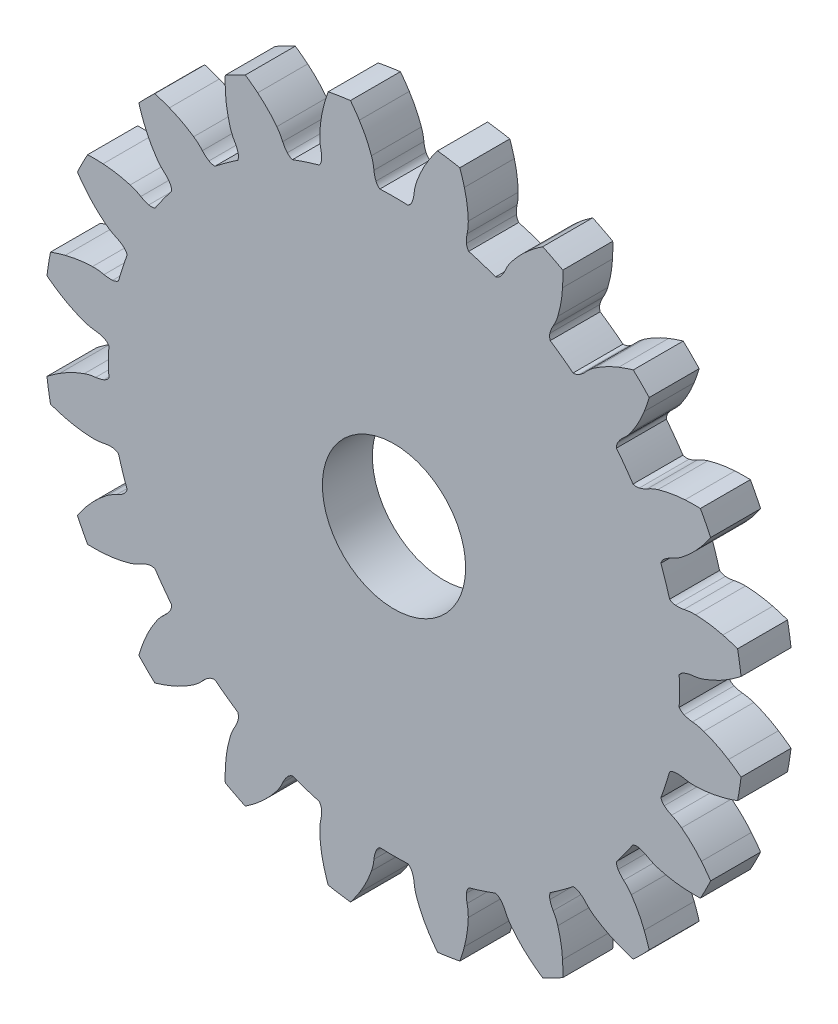
SolidWorks part; units mm, degrees
ref_plane "Front Plane" through (0, 0, 0) normal (0, 0, 1) x (1, 0, 0)
ref_plane "Top Plane" through (0, 0, 0) normal (0, 1, 0) x (1, 0, 0)
ref_plane "Right Plane" through (0, 0, 0) normal (1, 0, 0) x (0, 0, -1)
sketch "Model" plane through (0, 0, 0) normal (0, 0, 1) x (1, 0, 0)
  line L0 (-1.9599, -122.157) -> (1.9099, -120.8335)
  line L1 (1.9099, -120.8335) -> (1.9099, -119.1665)
  line L2 (1.9099, -119.1665) -> (-1.9599, -117.843)
  line L3 (-1.9599, -117.843) -> (-1.9599, -116.157)
  line L4 (-1.9599, -116.157) -> (1.9099, -114.8335)
  line L5 (1.9099, -114.8335) -> (1.9099, -113.1665)
  line L6 (1.9099, -113.1665) -> (-1.9599, -111.843)
  line L7 (-1.9599, -111.843) -> (-1.9599, -110.157)
  line L8 (-1.9599, -110.157) -> (1.9099, -108.8335)
  line L9 (1.9099, -108.8335) -> (1.9099, -107.1665)
  line L10 (1.9099, -107.1665) -> (-1.9599, -105.843)
  line L11 (-1.9599, -105.843) -> (-1.9599, -104.157)
  line L12 (-1.9599, -104.157) -> (1.9099, -102.8335)
  line L13 (1.9099, -102.8335) -> (1.9099, -101.1665)
  line L14 (1.9099, -101.1665) -> (-1.9599, -99.843)
  line L15 (-1.9599, -99.843) -> (-1.9599, -98.157)
  line L16 (-1.9599, -98.157) -> (1.9099, -96.8335)
  line L17 (1.9099, -96.8335) -> (1.9099, -95.1665)
  line L18 (1.9099, -95.1665) -> (-1.9599, -93.843)
  line L19 (-1.9599, -93.843) -> (-1.9599, -92.157)
  line L20 (-1.9599, -92.157) -> (1.9099, -90.8335)
  line L21 (1.9099, -90.8335) -> (1.9099, -89.1665)
  line L22 (1.9099, -89.1665) -> (-1.9599, -87.843)
  line L23 (-1.9599, -87.843) -> (-1.9599, -86.157)
  line L24 (-1.9599, -86.157) -> (1.9099, -84.8335)
  line L25 (1.9099, -84.8335) -> (1.9099, -83.1665)
  line L26 (1.9099, -83.1665) -> (-1.9599, -81.843)
  line L27 (-1.9599, -81.843) -> (-1.9599, -80.157)
  line L28 (-1.9599, -80.157) -> (1.9099, -78.8335)
  line L29 (1.9099, -78.8335) -> (1.9099, -77.1665)
  line L30 (1.9099, -77.1665) -> (-1.9599, -75.843)
  line L31 (-1.9599, -75.843) -> (-1.9599, -74.157)
  line L32 (-1.9599, -74.157) -> (1.9099, -72.8335)
  line L33 (1.9099, -72.8335) -> (1.9099, -71.1665)
  line L34 (1.9099, -71.1665) -> (-1.9599, -69.843)
  line L35 (-1.9599, -69.843) -> (-1.9599, -68.157)
  line L36 (-1.9599, -68.157) -> (1.9099, -66.8335)
  line L37 (1.9099, -66.8335) -> (1.9099, -65.1665)
  line L38 (1.9099, -65.1665) -> (-1.9599, -63.843)
  line L39 (-1.9599, -63.843) -> (-1.9599, -62.157)
  line L40 (-1.9599, -62.157) -> (1.9099, -60.8335)
  line L41 (1.9099, -60.8335) -> (1.9099, -59.1665)
  line L42 (1.9099, -59.1665) -> (-1.9599, -57.843)
  line L43 (-1.9599, -57.843) -> (-1.9599, -56.157)
  line L44 (-1.9599, -56.157) -> (1.9099, -54.8335)
  line L45 (1.9099, -54.8335) -> (1.9099, -53.1665)
  line L46 (1.9099, -53.1665) -> (-1.9599, -51.843)
  line L47 (-1.9599, -51.843) -> (-1.9599, -50.157)
  line L48 (-1.9599, -50.157) -> (1.9099, -48.8335)
  line L49 (1.9099, -48.8335) -> (1.9099, -47.1665)
  line L50 (1.9099, -47.1665) -> (-1.9599, -45.843)
  line L51 (-1.9599, -45.843) -> (-1.9599, -44.157)
  line L52 (-1.9599, -44.157) -> (1.9099, -42.8335)
  line L53 (1.9099, -42.8335) -> (1.9099, -41.1665)
  line L54 (1.9099, -41.1665) -> (-1.9599, -39.843)
  line L55 (-1.9599, -39.843) -> (-1.9599, -38.157)
  line L56 (-1.9599, -38.157) -> (1.9099, -36.8335)
  line L57 (1.9099, -36.8335) -> (1.9099, -35.1665)
  line L58 (1.9099, -35.1665) -> (-1.9599, -33.843)
  line L59 (-1.9599, -33.843) -> (-1.9599, -32.157)
  line L60 (-1.9599, -32.157) -> (1.9099, -30.8335)
  line L61 (1.9099, -30.8335) -> (1.9099, -29.1665)
  line L62 (1.9099, -29.1665) -> (-1.9599, -27.843)
  line L63 (-1.9599, -27.843) -> (-1.9599, -26.157)
  line L64 (-1.9599, -26.157) -> (1.9099, -24.8335)
  line L65 (1.9099, -24.8335) -> (1.9099, -23.1665)
  line L66 (1.9099, -23.1665) -> (-1.9599, -21.843)
  line L67 (-1.9599, -21.843) -> (-1.9599, -20.157)
  line L68 (-1.9599, -20.157) -> (1.9099, -18.8335)
  line L69 (1.9099, -18.8335) -> (1.9099, -17.1665)
  line L70 (1.9099, -17.1665) -> (-1.9599, -15.843)
  line L71 (-1.9599, -15.843) -> (-1.9599, -14.157)
  line L72 (-1.9599, -14.157) -> (1.9099, -12.8335)
  line L73 (1.9099, -12.8335) -> (1.9099, -11.1665)
  line L74 (1.9099, -11.1665) -> (-1.9599, -9.843)
  line L75 (-1.9599, -9.843) -> (-1.9599, -8.157)
  line L76 (-1.9599, -8.157) -> (1.9099, -6.8335)
  line L77 (1.9099, -6.8335) -> (1.9099, -5.1665)
  line L78 (1.9099, -5.1665) -> (-1.9599, -3.843)
  line L79 (-1.9599, -3.843) -> (-1.9599, -2.157)
  line L80 (-1.9599, -2.157) -> (1.9099, -0.8335)
  line L81 (1.9099, -0.8335) -> (1.9099, 0.8335)
  line L82 (1.9099, 0.8335) -> (-1.9599, 2.157)
  line L83 (-1.9599, 2.157) -> (-1.9599, 3.843)
  line L84 (-1.9599, 3.843) -> (1.9099, 5.1665)
  line L85 (1.9099, 5.1665) -> (1.9099, 6.8335)
  line L86 (1.9099, 6.8335) -> (-1.9599, 8.157)
  line L87 (-1.9599, 8.157) -> (-1.9599, 9.843)
  line L88 (-1.9599, 9.843) -> (1.9099, 11.1665)
  line L89 (1.9099, 11.1665) -> (1.9099, 12.8335)
  line L90 (1.9099, 12.8335) -> (-1.9599, 14.157)
  line L91 (-1.9599, 14.157) -> (-1.9599, 15.843)
  line L92 (-1.9599, 15.843) -> (1.9099, 17.1665)
  line L93 (1.9099, 17.1665) -> (1.9099, 18.8335)
  line L94 (1.9099, 18.8335) -> (-1.9599, 20.157)
  line L95 (-1.9599, 20.157) -> (-1.9599, 21.843)
  line L96 (-1.9599, 21.843) -> (1.9099, 23.1665)
  line L97 (1.9099, 23.1665) -> (1.9099, 24.8335)
  line L98 (1.9099, 24.8335) -> (-1.9599, 26.157)
  line L99 (-1.9599, 26.157) -> (-1.9599, 27.843)
  line L100 (-1.9599, 27.843) -> (1.9099, 29.1665)
  line L101 (1.9099, 29.1665) -> (1.9099, 30.8335)
  line L102 (1.9099, 30.8335) -> (-1.9599, 32.157)
  line L103 (-1.9599, 32.157) -> (-1.9599, 33.843)
  line L104 (-1.9599, 33.843) -> (1.9099, 35.1665)
  line L105 (1.9099, 35.1665) -> (1.9099, 36.8335)
  line L106 (1.9099, 36.8335) -> (-1.9599, 38.157)
  line L107 (-1.9599, 38.157) -> (-1.9599, 39.843)
  line L108 (-1.9599, 39.843) -> (1.9099, 41.1665)
  line L109 (1.9099, 41.1665) -> (1.9099, 42.8335)
  line L110 (1.9099, 42.8335) -> (-1.9599, 44.157)
  line L111 (-1.9599, 44.157) -> (-1.9599, 45.843)
  line L112 (-1.9599, 45.843) -> (1.9099, 47.1665)
  line L113 (1.9099, 47.1665) -> (1.9099, 48.8335)
  line L114 (1.9099, 48.8335) -> (-1.9599, 50.157)
  line L115 (-1.9599, 50.157) -> (-1.9599, 51.843)
  line L116 (-1.9599, 51.843) -> (1.9099, 53.1665)
  line L117 (1.9099, 53.1665) -> (1.9099, 54.8335)
  line L118 (1.9099, 54.8335) -> (-1.9599, 56.157)
  line L119 (-1.9599, 56.157) -> (-1.9599, 57.843)
  line L120 (-1.9599, 57.843) -> (1.9099, 59.1665)
  line L121 (1.9099, 59.1665) -> (1.9099, 60.8335)
  line L122 (1.9099, 60.8335) -> (-1.9599, 62.157)
  line L123 (-1.9599, 62.157) -> (-1.9599, 63.843)
  line L124 (-1.9599, 63.843) -> (1.9099, 65.1665)
  line L125 (1.9099, 65.1665) -> (1.9099, 66.8335)
  line L126 (1.9099, 66.8335) -> (-1.9599, 68.157)
  line L127 (-1.9599, 68.157) -> (-1.9599, 69.843)
  line L128 (-1.9599, 69.843) -> (1.9099, 71.1665)
  line L129 (1.9099, 71.1665) -> (1.9099, 72.8335)
  line L130 (1.9099, 72.8335) -> (-1.9599, 74.157)
  line L131 (-1.9599, 74.157) -> (-1.9599, 75.843)
  line L132 (-1.9599, 75.843) -> (1.9099, 77.1665)
  line L133 (1.9099, 77.1665) -> (1.9099, 78.8335)
  line L134 (1.9099, 78.8335) -> (-1.9599, 80.157)
  line L135 (-1.9599, 80.157) -> (-1.9599, 81.843)
  line L136 (-1.9599, 81.843) -> (1.9099, 83.1665)
  line L137 (1.9099, 83.1665) -> (1.9099, 84.8335)
  line L138 (1.9099, 84.8335) -> (-1.9599, 86.157)
  line L139 (-1.9599, 86.157) -> (-1.9599, 87.843)
  line L140 (-1.9599, 87.843) -> (1.9099, 89.1665)
  line L141 (1.9099, 89.1665) -> (1.9099, 90.8335)
  line L142 (1.9099, 90.8335) -> (-1.9599, 92.157)
  line L143 (-1.9599, 92.157) -> (-1.9599, 93.843)
  line L144 (-1.9599, 93.843) -> (1.9099, 95.1665)
  line L145 (1.9099, 95.1665) -> (1.9099, 96.8335)
  line L146 (1.9099, 96.8335) -> (-1.9599, 98.157)
  line L147 (-1.9599, 98.157) -> (-1.9599, 99.843)
  line L148 (-1.9599, 99.843) -> (1.9099, 101.1665)
  line L149 (1.9099, 101.1665) -> (1.9099, 102.8335)
  line L150 (1.9099, 102.8335) -> (-1.9599, 104.157)
  line L151 (-1.9599, 104.157) -> (-1.9599, 105.843)
  line L152 (-1.9599, 105.843) -> (1.9099, 107.1665)
  line L153 (1.9099, 107.1665) -> (1.9099, 108.8335)
  line L154 (1.9099, 108.8335) -> (-1.9599, 110.157)
  line L155 (-1.9599, 110.157) -> (-1.9599, 111.843)
  line L156 (-1.9599, 111.843) -> (1.9099, 113.1665)
  line L157 (1.9099, 113.1665) -> (1.9099, 114.8335)
  line L158 (1.9099, 114.8335) -> (-1.9599, 116.157)
  line L159 (-1.9599, 116.157) -> (-1.9599, 117.843)
  line L160 (-1.9599, 117.843) -> (1.9099, 119.1665)
  line L161 (1.9099, 119.1665) -> (1.9099, 120.8335)
  line L162 (1.9099, 120.8335) -> (-1.9599, 122.157)
  line L163 (-1.9599, 122.157) -> (-1.9599, 123)
  line L164 (-1.9599, 123) -> (-9.5993, 123)
  line L165 (-9.5993, 123) -> (-9.5993, -123)
  line L166 (-9.5993, -123) -> (-1.9599, -123)
  line L167 (-1.9599, -123) -> (-1.9599, -122.157)
  line L168 (-1.5377, 3.9366) -> (-1.6512, 3.2864)
  line L169 (-1.6512, 3.2864) -> (-1.7442, 2.6331)
  line L170 (-1.7442, 2.6331) -> (-1.7455, 2.6215)
  line L171 (-1.7455, 2.6215) -> (-1.7388, 2.6161)
  line L172 (-1.7388, 2.6161) -> (-1.4771, 2.4198)
  line L173 (-1.4771, 2.4198) -> (-1.2239, 2.242)
  line L174 (-1.2239, 2.242) -> (-0.9803, 2.082)
  line L175 (-0.9803, 2.082) -> (-0.7469, 1.9391)
  line L176 (-0.7469, 1.9391) -> (-0.5246, 1.8124)
  line L177 (-0.5246, 1.8124) -> (-0.3143, 1.7011)
  line L178 (-0.3143, 1.7011) -> (-0.1165, 1.6044)
  line L179 (-0.1165, 1.6044) -> (0.0679, 1.5212)
  line L180 (0.0679, 1.5212) -> (0.2383, 1.4506)
  line L181 (0.2383, 1.4506) -> (0.3942, 1.3918)
  line L182 (0.3942, 1.3918) -> (0.535, 1.3436)
  line L183 (0.535, 1.3436) -> (0.6602, 1.3051)
  line L184 (0.6602, 1.3051) -> (0.7694, 1.2753)
  line L185 (0.7694, 1.2753) -> (0.862, 1.2531)
  line L186 (0.862, 1.2531) -> (0.9379, 1.2374)
  line L187 (0.9379, 1.2374) -> (0.9966, 1.2272)
  line L188 (0.9966, 1.2272) -> (1.038, 1.2213)
  line L189 (1.038, 1.2213) -> (1.0618, 1.2187)
  line L190 (1.0618, 1.2187) -> (1.0916, 1.2164)
  line L191 (1.0916, 1.2164) -> (1.2696, 1.1958)
  line L192 (1.2696, 1.1958) -> (1.4284, 1.1659)
  line L193 (1.4284, 1.1659) -> (1.5676, 1.1277)
  line L194 (1.5676, 1.1277) -> (1.6869, 1.0826)
  line L195 (1.6869, 1.0826) -> (1.7859, 1.0316)
  line L196 (1.7859, 1.0316) -> (1.8646, 0.9761)
  line L197 (1.8646, 0.9761) -> (1.9226, 0.9172)
  line L198 (1.9226, 0.9172) -> (1.9599, 0.8563)
  line L199 (1.9599, 0.8563) -> (1.9764, 0.7945)
  line L200 (1.9764, 0.7945) -> (1.9599, 0.2692)
  line L201 (1.9599, 0.2692) -> (1.9599, -0.2692)
  line L202 (1.9599, -0.2692) -> (1.9764, -0.7945)
  line L203 (1.9764, -0.7945) -> (1.9599, -0.8563)
  line L204 (1.9599, -0.8563) -> (1.9226, -0.9172)
  line L205 (1.9226, -0.9172) -> (1.8646, -0.9761)
  line L206 (1.8646, -0.9761) -> (1.7859, -1.0316)
  line L207 (1.7859, -1.0316) -> (1.6869, -1.0826)
  line L208 (1.6869, -1.0826) -> (1.5676, -1.1277)
  line L209 (1.5676, -1.1277) -> (1.4284, -1.1659)
  line L210 (1.4284, -1.1659) -> (1.2696, -1.1958)
  line L211 (1.2696, -1.1958) -> (1.0916, -1.2164)
  line L212 (1.0916, -1.2164) -> (1.0618, -1.2187)
  line L213 (1.0618, -1.2187) -> (1.038, -1.2213)
  line L214 (1.038, -1.2213) -> (0.9966, -1.2272)
  line L215 (0.9966, -1.2272) -> (0.9379, -1.2374)
  line L216 (0.9379, -1.2374) -> (0.862, -1.2531)
  line L217 (0.862, -1.2531) -> (0.7694, -1.2753)
  line L218 (0.7694, -1.2753) -> (0.6602, -1.3051)
  line L219 (0.6602, -1.3051) -> (0.535, -1.3436)
  line L220 (0.535, -1.3436) -> (0.3942, -1.3918)
  line L221 (0.3942, -1.3918) -> (0.2383, -1.4506)
  line L222 (0.2383, -1.4506) -> (0.0679, -1.5212)
  line L223 (0.0679, -1.5212) -> (-0.1165, -1.6044)
  line L224 (-0.1165, -1.6044) -> (-0.3143, -1.7011)
  line L225 (-0.3143, -1.7011) -> (-0.5246, -1.8124)
  line L226 (-0.5246, -1.8124) -> (-0.7469, -1.9391)
  line L227 (-0.7469, -1.9391) -> (-0.9803, -2.082)
  line L228 (-0.9803, -2.082) -> (-1.2239, -2.242)
  line L229 (-1.2239, -2.242) -> (-1.4771, -2.4198)
  line L230 (-1.4771, -2.4198) -> (-1.7388, -2.6161)
  line L231 (-1.7388, -2.6161) -> (-1.7455, -2.6215)
  line L232 (-1.7455, -2.6215) -> (-1.7442, -2.6331)
  line L233 (-1.7442, -2.6331) -> (-1.6512, -3.2864)
  line L234 (-1.6512, -3.2864) -> (-1.5377, -3.9366)
  line L235 (-1.5377, -3.9366) -> (-1.5354, -3.948)
  line L236 (-1.5354, -3.948) -> (-1.5274, -3.951)
  line L237 (-1.5274, -3.951) -> (-1.2178, -4.0569)
  line L238 (-1.2178, -4.0569) -> (-0.9221, -4.1477)
  line L239 (-0.9221, -4.1477) -> (-0.6409, -4.2246)
  line L240 (-0.6409, -4.2246) -> (-0.3748, -4.2884)
  line L241 (-0.3748, -4.2884) -> (-0.1243, -4.3402)
  line L242 (-0.1243, -4.3402) -> (0.1102, -4.381)
  line L243 (0.1102, -4.381) -> (0.3281, -4.412)
  line L244 (0.3281, -4.412) -> (0.5292, -4.4341)
  line L245 (0.5292, -4.4341) -> (0.7132, -4.4485)
  line L246 (0.7132, -4.4485) -> (0.8796, -4.4563)
  line L247 (0.8796, -4.4563) -> (1.0284, -4.4586)
  line L248 (1.0284, -4.4586) -> (1.1593, -4.4565)
  line L249 (1.1593, -4.4565) -> (1.2724, -4.4511)
  line L250 (1.2724, -4.4511) -> (1.3673, -4.4436)
  line L251 (1.3673, -4.4436) -> (1.4443, -4.4351)
  line L252 (1.4443, -4.4351) -> (1.5034, -4.4267)
  line L253 (1.5034, -4.4267) -> (1.5445, -4.4195)
  line L254 (1.5445, -4.4195) -> (1.568, -4.4146)
  line L255 (1.568, -4.4146) -> (1.5971, -4.4076)
  line L256 (1.5971, -4.4076) -> (1.7727, -4.3722)
  line L257 (1.7727, -4.3722) -> (1.933, -4.3516)
  line L258 (1.933, -4.3516) -> (2.0771, -4.3448)
  line L259 (2.0771, -4.3448) -> (2.2045, -4.3509)
  line L260 (2.2045, -4.3509) -> (2.3145, -4.3688)
  line L261 (2.3145, -4.3688) -> (2.4064, -4.3973)
  line L262 (2.4064, -4.3973) -> (2.4798, -4.4353)
  line L263 (2.4798, -4.4353) -> (2.5341, -4.4818)
  line L264 (2.5341, -4.4818) -> (2.5689, -4.5354)
  line L265 (2.5689, -4.5354) -> (2.7155, -5.0401)
  line L266 (2.7155, -5.0401) -> (2.8819, -5.5522)
  line L267 (2.8819, -5.5522) -> (3.0599, -6.0467)
  line L268 (3.0599, -6.0467) -> (3.0633, -6.1105)
  line L269 (3.0633, -6.1105) -> (3.0467, -6.18)
  line L270 (3.0467, -6.18) -> (3.0097, -6.2539)
  line L271 (3.0097, -6.2539) -> (2.9521, -6.331)
  line L272 (2.9521, -6.331) -> (2.8736, -6.4101)
  line L273 (2.8736, -6.4101) -> (2.7741, -6.4899)
  line L274 (2.7741, -6.4899) -> (2.6535, -6.5692)
  line L275 (2.6535, -6.5692) -> (2.5118, -6.6468)
  line L276 (2.5118, -6.6468) -> (2.3488, -6.7213)
  line L277 (2.3488, -6.7213) -> (2.3212, -6.7327)
  line L278 (2.3212, -6.7327) -> (2.2993, -6.7426)
  line L279 (2.2993, -6.7426) -> (2.2618, -6.761)
  line L280 (2.2618, -6.761) -> (2.2091, -6.7888)
  line L281 (2.2091, -6.7888) -> (2.1418, -6.8272)
  line L282 (2.1418, -6.8272) -> (2.0605, -6.877)
  line L283 (2.0605, -6.877) -> (1.966, -6.939)
  line L284 (1.966, -6.939) -> (1.8588, -7.0143)
  line L285 (1.8588, -7.0143) -> (1.7398, -7.1036)
  line L286 (1.7398, -7.1036) -> (1.6097, -7.2078)
  line L287 (1.6097, -7.2078) -> (1.4694, -7.3275)
  line L288 (1.4694, -7.3275) -> (1.3197, -7.4636)
  line L289 (1.3197, -7.4636) -> (1.1616, -7.6168)
  line L290 (1.1616, -7.6168) -> (0.9959, -7.7876)
  line L291 (0.9959, -7.7876) -> (0.8236, -7.9768)
  line L292 (0.8236, -7.9768) -> (0.6459, -8.1848)
  line L293 (0.6459, -8.1848) -> (0.4635, -8.4123)
  line L294 (0.4635, -8.4123) -> (0.2777, -8.6596)
  line L295 (0.2777, -8.6596) -> (0.0895, -8.9272)
  line L296 (0.0895, -8.9272) -> (0.0848, -8.9344)
  line L297 (0.0848, -8.9344) -> (0.0896, -8.945)
  line L298 (0.0896, -8.945) -> (0.3799, -9.5376)
  line L299 (0.3799, -9.5376) -> (0.6887, -10.1209)
  line L300 (0.6887, -10.1209) -> (0.6945, -10.131)
  line L301 (0.6945, -10.131) -> (0.7031, -10.1314)
  line L302 (0.7031, -10.1314) -> (1.0302, -10.1364)
  line L303 (1.0302, -10.1364) -> (1.3395, -10.1315)
  line L304 (1.3395, -10.1315) -> (1.6307, -10.1177)
  line L305 (1.6307, -10.1177) -> (1.9035, -10.0961)
  line L306 (1.9035, -10.0961) -> (2.1578, -10.0679)
  line L307 (2.1578, -10.0679) -> (2.3934, -10.0343)
  line L308 (2.3934, -10.0343) -> (2.6102, -9.9964)
  line L309 (2.6102, -9.9964) -> (2.8083, -9.9553)
  line L310 (2.8083, -9.9553) -> (2.9877, -9.9122)
  line L311 (2.9877, -9.9122) -> (3.1484, -9.8682)
  line L312 (3.1484, -9.8682) -> (3.2906, -9.8244)
  line L313 (3.2906, -9.8244) -> (3.4145, -9.7819)
  line L314 (3.4145, -9.7819) -> (3.5203, -9.7419)
  line L315 (3.5203, -9.7419) -> (3.6083, -9.7054)
  line L316 (3.6083, -9.7054) -> (3.6789, -9.6735)
  line L317 (3.6789, -9.6735) -> (3.7324, -9.6473)
  line L318 (3.7324, -9.6473) -> (3.7694, -9.6277)
  line L319 (3.7694, -9.6277) -> (3.7902, -9.6158)
  line L320 (3.7902, -9.6158) -> (3.8157, -9.6002)
  line L321 (3.8157, -9.6002) -> (3.9718, -9.5122)
  line L322 (3.9718, -9.5122) -> (4.1178, -9.4431)
  line L323 (4.1178, -9.4431) -> (4.2529, -9.3921)
  line L324 (4.2529, -9.3921) -> (4.3759, -9.3585)
  line L325 (4.3759, -9.3585) -> (4.486, -9.3415)
  line L326 (4.486, -9.3415) -> (4.5822, -9.3402)
  line L327 (4.5822, -9.3402) -> (4.6638, -9.3538)
  line L328 (4.6638, -9.3538) -> (4.7297, -9.3811)
  line L329 (4.7297, -9.3811) -> (4.7794, -9.4214)
  line L330 (4.7794, -9.4214) -> (5.0748, -9.8561)
  line L331 (5.0748, -9.8561) -> (5.3913, -10.2917)
  line L332 (5.3913, -10.2917) -> (5.7134, -10.707)
  line L333 (5.7134, -10.707) -> (5.7364, -10.7667)
  line L334 (5.7364, -10.7667) -> (5.742, -10.8379)
  line L335 (5.742, -10.8379) -> (5.7297, -10.9196)
  line L336 (5.7297, -10.9196) -> (5.6987, -11.0107)
  line L337 (5.6987, -11.0107) -> (5.6485, -11.1102)
  line L338 (5.6485, -11.1102) -> (5.5786, -11.2168)
  line L339 (5.5786, -11.2168) -> (5.4884, -11.3295)
  line L340 (5.4884, -11.3295) -> (5.3775, -11.447)
  line L341 (5.3775, -11.447) -> (5.2456, -11.5683)
  line L342 (5.2456, -11.5683) -> (5.2228, -11.5877)
  line L343 (5.2228, -11.5877) -> (5.2051, -11.6038)
  line L344 (5.2051, -11.6038) -> (5.1751, -11.6329)
  line L345 (5.1751, -11.6329) -> (5.1336, -11.6757)
  line L346 (5.1336, -11.6757) -> (5.0815, -11.733)
  line L347 (5.0815, -11.733) -> (5.0195, -11.8054)
  line L348 (5.0195, -11.8054) -> (4.9488, -11.8937)
  line L349 (4.9488, -11.8937) -> (4.8701, -11.9984)
  line L350 (4.8701, -11.9984) -> (4.7845, -12.1201)
  line L351 (4.7845, -12.1201) -> (4.693, -12.2594)
  line L352 (4.693, -12.2594) -> (4.5965, -12.4166)
  line L353 (4.5965, -12.4166) -> (4.4962, -12.5923)
  line L354 (4.4962, -12.5923) -> (4.3932, -12.7868)
  line L355 (4.3932, -12.7868) -> (4.2884, -13.0005)
  line L356 (4.2884, -13.0005) -> (4.1831, -13.2337)
  line L357 (4.1831, -13.2337) -> (4.0782, -13.4865)
  line L358 (4.0782, -13.4865) -> (3.9751, -13.7591)
  line L359 (3.9751, -13.7591) -> (3.8748, -14.0517)
  line L360 (3.8748, -14.0517) -> (3.7785, -14.3644)
  line L361 (3.7785, -14.3644) -> (3.7763, -14.3727)
  line L362 (3.7763, -14.3727) -> (3.7841, -14.3813)
  line L363 (3.7841, -14.3813) -> (4.2434, -14.8552)
  line L364 (4.2434, -14.8552) -> (4.7173, -15.3145)
  line L365 (4.7173, -15.3145) -> (4.7259, -15.3223)
  line L366 (4.7259, -15.3223) -> (4.7342, -15.3201)
  line L367 (4.7342, -15.3201) -> (5.0469, -15.2238)
  line L368 (5.0469, -15.2238) -> (5.3395, -15.1235)
  line L369 (5.3395, -15.1235) -> (5.6121, -15.0203)
  line L370 (5.6121, -15.0203) -> (5.8649, -14.9155)
  line L371 (5.8649, -14.9155) -> (6.0981, -14.8102)
  line L372 (6.0981, -14.8102) -> (6.3117, -14.7054)
  line L373 (6.3117, -14.7054) -> (6.5063, -14.6023)
  line L374 (6.5063, -14.6023) -> (6.682, -14.5021)
  line L375 (6.682, -14.5021) -> (6.8392, -14.4056)
  line L376 (6.8392, -14.4056) -> (6.9785, -14.3141)
  line L377 (6.9785, -14.3141) -> (7.1002, -14.2285)
  line L378 (7.1002, -14.2285) -> (7.2049, -14.1498)
  line L379 (7.2049, -14.1498) -> (7.2932, -14.0791)
  line L380 (7.2932, -14.0791) -> (7.3656, -14.0171)
  line L381 (7.3656, -14.0171) -> (7.4229, -13.965)
  line L382 (7.4229, -13.965) -> (7.4657, -13.9235)
  line L383 (7.4657, -13.9235) -> (7.4948, -13.8935)
  line L384 (7.4948, -13.8935) -> (7.5109, -13.8758)
  line L385 (7.5109, -13.8758) -> (7.5303, -13.853)
  line L386 (7.5303, -13.853) -> (7.6515, -13.7211)
  line L387 (7.6515, -13.7211) -> (7.7691, -13.6102)
  line L388 (7.7691, -13.6102) -> (7.8818, -13.52)
  line L389 (7.8818, -13.52) -> (7.9884, -13.4501)
  line L390 (7.9884, -13.4501) -> (8.0879, -13.3999)
  line L391 (8.0879, -13.3999) -> (8.179, -13.3689)
  line L392 (8.179, -13.3689) -> (8.2607, -13.3566)
  line L393 (8.2607, -13.3566) -> (8.3319, -13.3622)
  line L394 (8.3319, -13.3622) -> (8.3916, -13.3852)
  line L395 (8.3916, -13.3852) -> (8.8069, -13.7073)
  line L396 (8.8069, -13.7073) -> (9.2425, -14.0238)
  line L397 (9.2425, -14.0238) -> (9.6772, -14.3192)
  line L398 (9.6772, -14.3192) -> (9.7175, -14.3688)
  line L399 (9.7175, -14.3688) -> (9.7448, -14.4348)
  line L400 (9.7448, -14.4348) -> (9.7584, -14.5164)
  line L401 (9.7584, -14.5164) -> (9.7571, -14.6126)
  line L402 (9.7571, -14.6126) -> (9.7401, -14.7227)
  line L403 (9.7401, -14.7227) -> (9.7065, -14.8457)
  line L404 (9.7065, -14.8457) -> (9.6555, -14.9808)
  line L405 (9.6555, -14.9808) -> (9.5864, -15.1268)
  line L406 (9.5864, -15.1268) -> (9.4984, -15.2829)
  line L407 (9.4984, -15.2829) -> (9.4828, -15.3084)
  line L408 (9.4828, -15.3084) -> (9.4709, -15.3292)
  line L409 (9.4709, -15.3292) -> (9.4513, -15.3661)
  line L410 (9.4513, -15.3661) -> (9.4251, -15.4197)
  line L411 (9.4251, -15.4197) -> (9.3932, -15.4903)
  line L412 (9.3932, -15.4903) -> (9.3567, -15.5783)
  line L413 (9.3567, -15.5783) -> (9.3167, -15.6841)
  line L414 (9.3167, -15.6841) -> (9.2742, -15.808)
  line L415 (9.2742, -15.808) -> (9.2304, -15.9502)
  line L416 (9.2304, -15.9502) -> (9.1864, -16.1109)
  line L417 (9.1864, -16.1109) -> (9.1433, -16.2903)
  line L418 (9.1433, -16.2903) -> (9.1022, -16.4884)
  line L419 (9.1022, -16.4884) -> (9.0643, -16.7052)
  line L420 (9.0643, -16.7052) -> (9.0307, -16.9408)
  line L421 (9.0307, -16.9408) -> (9.0025, -17.1951)
  line L422 (9.0025, -17.1951) -> (8.9809, -17.4679)
  line L423 (8.9809, -17.4679) -> (8.9671, -17.7591)
  line L424 (8.9671, -17.7591) -> (8.9622, -18.0684)
  line L425 (8.9622, -18.0684) -> (8.9672, -18.3955)
  line L426 (8.9672, -18.3955) -> (8.9676, -18.4041)
  line L427 (8.9676, -18.4041) -> (8.9777, -18.4098)
  line L428 (8.9777, -18.4098) -> (9.561, -18.7187)
  line L429 (9.561, -18.7187) -> (10.1536, -19.009)
  line L430 (10.1536, -19.009) -> (10.1642, -19.0138)
  line L431 (10.1642, -19.0138) -> (10.1714, -19.0091)
  line L432 (10.1714, -19.0091) -> (10.439, -18.8209)
  line L433 (10.439, -18.8209) -> (10.6863, -18.6351)
  line L434 (10.6863, -18.6351) -> (10.9138, -18.4527)
  line L435 (10.9138, -18.4527) -> (11.1218, -18.2749)
  line L436 (11.1218, -18.2749) -> (11.311, -18.1027)
  line L437 (11.311, -18.1027) -> (11.4818, -17.937)
  line L438 (11.4818, -17.937) -> (11.635, -17.7789)
  line L439 (11.635, -17.7789) -> (11.7711, -17.6292)
  line L440 (11.7711, -17.6292) -> (11.8908, -17.4889)
  line L441 (11.8908, -17.4889) -> (11.995, -17.3588)
  line L442 (11.995, -17.3588) -> (12.0843, -17.2398)
  line L443 (12.0843, -17.2398) -> (12.1596, -17.1326)
  line L444 (12.1596, -17.1326) -> (12.2216, -17.038)
  line L445 (12.2216, -17.038) -> (12.2714, -16.9568)
  line L446 (12.2714, -16.9568) -> (12.3098, -16.8895)
  line L447 (12.3098, -16.8895) -> (12.3376, -16.8368)
  line L448 (12.3376, -16.8368) -> (12.356, -16.7993)
  line L449 (12.356, -16.7993) -> (12.3659, -16.7774)
  line L450 (12.3659, -16.7774) -> (12.3773, -16.7498)
  line L451 (12.3773, -16.7498) -> (12.4518, -16.5868)
  line L452 (12.4518, -16.5868) -> (12.5294, -16.4451)
  line L453 (12.5294, -16.4451) -> (12.6087, -16.3245)
  line L454 (12.6087, -16.3245) -> (12.6885, -16.225)
  line L455 (12.6885, -16.225) -> (12.7676, -16.1465)
  line L456 (12.7676, -16.1465) -> (12.8447, -16.0889)
  line L457 (12.8447, -16.0889) -> (12.9186, -16.0519)
  line L458 (12.9186, -16.0519) -> (12.9881, -16.0353)
  line L459 (12.9881, -16.0353) -> (13.0519, -16.0387)
  line L460 (13.0519, -16.0387) -> (13.5464, -16.2167)
  line L461 (13.5464, -16.2167) -> (14.0585, -16.3831)
  line L462 (14.0585, -16.3831) -> (14.5632, -16.5297)
  line L463 (14.5632, -16.5297) -> (14.6168, -16.5645)
  line L464 (14.6168, -16.5645) -> (14.6633, -16.6188)
  line L465 (14.6633, -16.6188) -> (14.7013, -16.6922)
  line L466 (14.7013, -16.6922) -> (14.7298, -16.7841)
  line L467 (14.7298, -16.7841) -> (14.7477, -16.8941)
  line L468 (14.7477, -16.8941) -> (14.7538, -17.0214)
  line L469 (14.7538, -17.0214) -> (14.747, -17.1656)
  line L470 (14.747, -17.1656) -> (14.7264, -17.3259)
  line L471 (14.7264, -17.3259) -> (14.691, -17.5015)
  line L472 (14.691, -17.5015) -> (14.684, -17.5306)
  line L473 (14.684, -17.5306) -> (14.6791, -17.5541)
  line L474 (14.6791, -17.5541) -> (14.6719, -17.5952)
  line L475 (14.6719, -17.5952) -> (14.6635, -17.6543)
  line L476 (14.6635, -17.6543) -> (14.655, -17.7312)
  line L477 (14.655, -17.7312) -> (14.6475, -17.8262)
  line L478 (14.6475, -17.8262) -> (14.6421, -17.9392)
  line L479 (14.6421, -17.9392) -> (14.64, -18.0702)
  line L480 (14.64, -18.0702) -> (14.6423, -18.219)
  line L481 (14.6423, -18.219) -> (14.6501, -18.3854)
  line L482 (14.6501, -18.3854) -> (14.6645, -18.5693)
  line L483 (14.6645, -18.5693) -> (14.6866, -18.7704)
  line L484 (14.6866, -18.7704) -> (14.7176, -18.9884)
  line L485 (14.7176, -18.9884) -> (14.7584, -19.2229)
  line L486 (14.7584, -19.2229) -> (14.8102, -19.4734)
  line L487 (14.8102, -19.4734) -> (14.874, -19.7395)
  line L488 (14.874, -19.7395) -> (14.9508, -20.0207)
  line L489 (14.9508, -20.0207) -> (15.0417, -20.3164)
  line L490 (15.0417, -20.3164) -> (15.1476, -20.6259)
  line L491 (15.1476, -20.6259) -> (15.1506, -20.634)
  line L492 (15.1506, -20.634) -> (15.162, -20.6363)
  line L493 (15.162, -20.6363) -> (15.8121, -20.7498)
  line L494 (15.8121, -20.7498) -> (16.4655, -20.8428)
  line L495 (16.4655, -20.8428) -> (16.4771, -20.8441)
  line L496 (16.4771, -20.8441) -> (16.4825, -20.8374)
  line L497 (16.4825, -20.8374) -> (16.6788, -20.5757)
  line L498 (16.6788, -20.5757) -> (16.8566, -20.3225)
  line L499 (16.8566, -20.3225) -> (17.0166, -20.0789)
  line L500 (17.0166, -20.0789) -> (17.1595, -19.8455)
  line L501 (17.1595, -19.8455) -> (17.2862, -19.6232)
  line L502 (17.2862, -19.6232) -> (17.3974, -19.4129)
  line L503 (17.3974, -19.4129) -> (17.4942, -19.2151)
  line L504 (17.4942, -19.2151) -> (17.5774, -19.0307)
  line L505 (17.5774, -19.0307) -> (17.648, -18.8603)
  line L506 (17.648, -18.8603) -> (17.7068, -18.7044)
  line L507 (17.7068, -18.7044) -> (17.755, -18.5636)
  line L508 (17.755, -18.5636) -> (17.7935, -18.4384)
  line L509 (17.7935, -18.4384) -> (17.8233, -18.3292)
  line L510 (17.8233, -18.3292) -> (17.8455, -18.2366)
  line L511 (17.8455, -18.2366) -> (17.8612, -18.1607)
  line L512 (17.8612, -18.1607) -> (17.8714, -18.102)
  line L513 (17.8714, -18.102) -> (17.8773, -18.0606)
  line L514 (17.8773, -18.0606) -> (17.8799, -18.0368)
  line L515 (17.8799, -18.0368) -> (17.8822, -18.007)
  line L516 (17.8822, -18.007) -> (17.9028, -17.829)
  line L517 (17.9028, -17.829) -> (17.9327, -17.6702)
  line L518 (17.9327, -17.6702) -> (17.9709, -17.531)
  line L519 (17.9709, -17.531) -> (18.016, -17.4117)
  line L520 (18.016, -17.4117) -> (18.067, -17.3127)
  line L521 (18.067, -17.3127) -> (18.1225, -17.234)
  line L522 (18.1225, -17.234) -> (18.1814, -17.176)
  line L523 (18.1814, -17.176) -> (18.2423, -17.1387)
  line L524 (18.2423, -17.1387) -> (18.3041, -17.1222)
  line L525 (18.3041, -17.1222) -> (18.8294, -17.1387)
  line L526 (18.8294, -17.1387) -> (19.3678, -17.1387)
  line L527 (19.3678, -17.1387) -> (19.8931, -17.1222)
  line L528 (19.8931, -17.1222) -> (19.9549, -17.1387)
  line L529 (19.9549, -17.1387) -> (20.0158, -17.176)
  line L530 (20.0158, -17.176) -> (20.0747, -17.234)
  line L531 (20.0747, -17.234) -> (20.1302, -17.3127)
  line L532 (20.1302, -17.3127) -> (20.1812, -17.4117)
  line L533 (20.1812, -17.4117) -> (20.2263, -17.531)
  line L534 (20.2263, -17.531) -> (20.2645, -17.6702)
  line L535 (20.2645, -17.6702) -> (20.2944, -17.829)
  line L536 (20.2944, -17.829) -> (20.315, -18.007)
  line L537 (20.315, -18.007) -> (20.3173, -18.0368)
  line L538 (20.3173, -18.0368) -> (20.3199, -18.0606)
  line L539 (20.3199, -18.0606) -> (20.3258, -18.102)
  line L540 (20.3258, -18.102) -> (20.336, -18.1607)
  line L541 (20.336, -18.1607) -> (20.3517, -18.2366)
  line L542 (20.3517, -18.2366) -> (20.3739, -18.3292)
  line L543 (20.3739, -18.3292) -> (20.4037, -18.4384)
  line L544 (20.4037, -18.4384) -> (20.4422, -18.5636)
  line L545 (20.4422, -18.5636) -> (20.4904, -18.7044)
  line L546 (20.4904, -18.7044) -> (20.5492, -18.8603)
  line L547 (20.5492, -18.8603) -> (20.6198, -19.0307)
  line L548 (20.6198, -19.0307) -> (20.703, -19.2151)
  line L549 (20.703, -19.2151) -> (20.7997, -19.4129)
  line L550 (20.7997, -19.4129) -> (20.911, -19.6232)
  line L551 (20.911, -19.6232) -> (21.0377, -19.8455)
  line L552 (21.0377, -19.8455) -> (21.1806, -20.0789)
  line L553 (21.1806, -20.0789) -> (21.3406, -20.3225)
  line L554 (21.3406, -20.3225) -> (21.5184, -20.5757)
  line L555 (21.5184, -20.5757) -> (21.7147, -20.8374)
  line L556 (21.7147, -20.8374) -> (21.7201, -20.8441)
  line L557 (21.7201, -20.8441) -> (21.7317, -20.8428)
  line L558 (21.7317, -20.8428) -> (22.385, -20.7498)
  line L559 (22.385, -20.7498) -> (23.0352, -20.6363)
  line L560 (23.0352, -20.6363) -> (23.0466, -20.634)
  line L561 (23.0466, -20.634) -> (23.0496, -20.6259)
  line L562 (23.0496, -20.6259) -> (23.1555, -20.3164)
  line L563 (23.1555, -20.3164) -> (23.2463, -20.0207)
  line L564 (23.2463, -20.0207) -> (23.3232, -19.7395)
  line L565 (23.3232, -19.7395) -> (23.387, -19.4734)
  line L566 (23.387, -19.4734) -> (23.4388, -19.2229)
  line L567 (23.4388, -19.2229) -> (23.4796, -18.9884)
  line L568 (23.4796, -18.9884) -> (23.5106, -18.7704)
  line L569 (23.5106, -18.7704) -> (23.5327, -18.5693)
  line L570 (23.5327, -18.5693) -> (23.5471, -18.3854)
  line L571 (23.5471, -18.3854) -> (23.5549, -18.219)
  line L572 (23.5549, -18.219) -> (23.5572, -18.0702)
  line L573 (23.5572, -18.0702) -> (23.5551, -17.9392)
  line L574 (23.5551, -17.9392) -> (23.5497, -17.8262)
  line L575 (23.5497, -17.8262) -> (23.5422, -17.7312)
  line L576 (23.5422, -17.7312) -> (23.5337, -17.6543)
  line L577 (23.5337, -17.6543) -> (23.5253, -17.5952)
  line L578 (23.5253, -17.5952) -> (23.5181, -17.5541)
  line L579 (23.5181, -17.5541) -> (23.5132, -17.5306)
  line L580 (23.5132, -17.5306) -> (23.5062, -17.5015)
  line L581 (23.5062, -17.5015) -> (23.4708, -17.3259)
  line L582 (23.4708, -17.3259) -> (23.4502, -17.1656)
  line L583 (23.4502, -17.1656) -> (23.4434, -17.0214)
  line L584 (23.4434, -17.0214) -> (23.4495, -16.8941)
  line L585 (23.4495, -16.8941) -> (23.4674, -16.7841)
  line L586 (23.4674, -16.7841) -> (23.4959, -16.6922)
  line L587 (23.4959, -16.6922) -> (23.5339, -16.6188)
  line L588 (23.5339, -16.6188) -> (23.5804, -16.5645)
  line L589 (23.5804, -16.5645) -> (23.634, -16.5297)
  line L590 (23.634, -16.5297) -> (24.1387, -16.3831)
  line L591 (24.1387, -16.3831) -> (24.6508, -16.2167)
  line L592 (24.6508, -16.2167) -> (25.1453, -16.0387)
  line L593 (25.1453, -16.0387) -> (25.2091, -16.0353)
  line L594 (25.2091, -16.0353) -> (25.2786, -16.0519)
  line L595 (25.2786, -16.0519) -> (25.3525, -16.0889)
  line L596 (25.3525, -16.0889) -> (25.4296, -16.1465)
  line L597 (25.4296, -16.1465) -> (25.5087, -16.225)
  line L598 (25.5087, -16.225) -> (25.5885, -16.3245)
  line L599 (25.5885, -16.3245) -> (25.6678, -16.4451)
  line L600 (25.6678, -16.4451) -> (25.7453, -16.5868)
  line L601 (25.7453, -16.5868) -> (25.8199, -16.7498)
  line L602 (25.8199, -16.7498) -> (25.8313, -16.7774)
  line L603 (25.8313, -16.7774) -> (25.8412, -16.7993)
  line L604 (25.8412, -16.7993) -> (25.8595, -16.8368)
  line L605 (25.8595, -16.8368) -> (25.8874, -16.8895)
  line L606 (25.8874, -16.8895) -> (25.9258, -16.9568)
  line L607 (25.9258, -16.9568) -> (25.9755, -17.038)
  line L608 (25.9755, -17.038) -> (26.0376, -17.1326)
  line L609 (26.0376, -17.1326) -> (26.1129, -17.2398)
  line L610 (26.1129, -17.2398) -> (26.2022, -17.3588)
  line L611 (26.2022, -17.3588) -> (26.3064, -17.4889)
  line L612 (26.3064, -17.4889) -> (26.4261, -17.6292)
  line L613 (26.4261, -17.6292) -> (26.5622, -17.7789)
  line L614 (26.5622, -17.7789) -> (26.7154, -17.937)
  line L615 (26.7154, -17.937) -> (26.8862, -18.1027)
  line L616 (26.8862, -18.1027) -> (27.0754, -18.2749)
  line L617 (27.0754, -18.2749) -> (27.2834, -18.4527)
  line L618 (27.2834, -18.4527) -> (27.5109, -18.6351)
  line L619 (27.5109, -18.6351) -> (27.7582, -18.8209)
  line L620 (27.7582, -18.8209) -> (28.0258, -19.0091)
  line L621 (28.0258, -19.0091) -> (28.033, -19.0138)
  line L622 (28.033, -19.0138) -> (28.0436, -19.009)
  line L623 (28.0436, -19.009) -> (28.6362, -18.7187)
  line L624 (28.6362, -18.7187) -> (29.2195, -18.4098)
  line L625 (29.2195, -18.4098) -> (29.2296, -18.4041)
  line L626 (29.2296, -18.4041) -> (29.23, -18.3955)
  line L627 (29.23, -18.3955) -> (29.235, -18.0684)
  line L628 (29.235, -18.0684) -> (29.2301, -17.7591)
  line L629 (29.2301, -17.7591) -> (29.2162, -17.4679)
  line L630 (29.2162, -17.4679) -> (29.1947, -17.1951)
  line L631 (29.1947, -17.1951) -> (29.1665, -16.9408)
  line L632 (29.1665, -16.9408) -> (29.1329, -16.7052)
  line L633 (29.1329, -16.7052) -> (29.095, -16.4884)
  line L634 (29.095, -16.4884) -> (29.0539, -16.2903)
  line L635 (29.0539, -16.2903) -> (29.0108, -16.1109)
  line L636 (29.0108, -16.1109) -> (28.9668, -15.9502)
  line L637 (28.9668, -15.9502) -> (28.923, -15.808)
  line L638 (28.923, -15.808) -> (28.8805, -15.6841)
  line L639 (28.8805, -15.6841) -> (28.8405, -15.5783)
  line L640 (28.8405, -15.5783) -> (28.804, -15.4903)
  line L641 (28.804, -15.4903) -> (28.7721, -15.4197)
  line L642 (28.7721, -15.4197) -> (28.7459, -15.3661)
  line L643 (28.7459, -15.3661) -> (28.7263, -15.3292)
  line L644 (28.7263, -15.3292) -> (28.7144, -15.3084)
  line L645 (28.7144, -15.3084) -> (28.6988, -15.2829)
  line L646 (28.6988, -15.2829) -> (28.6108, -15.1268)
  line L647 (28.6108, -15.1268) -> (28.5416, -14.9808)
  line L648 (28.5416, -14.9808) -> (28.4907, -14.8457)
  line L649 (28.4907, -14.8457) -> (28.4571, -14.7227)
  line L650 (28.4571, -14.7227) -> (28.4401, -14.6126)
  line L651 (28.4401, -14.6126) -> (28.4388, -14.5164)
  line L652 (28.4388, -14.5164) -> (28.4523, -14.4348)
  line L653 (28.4523, -14.4348) -> (28.4797, -14.3688)
  line L654 (28.4797, -14.3688) -> (28.52, -14.3192)
  line L655 (28.52, -14.3192) -> (28.9547, -14.0238)
  line L656 (28.9547, -14.0238) -> (29.3903, -13.7073)
  line L657 (29.3903, -13.7073) -> (29.8056, -13.3852)
  line L658 (29.8056, -13.3852) -> (29.8652, -13.3622)
  line L659 (29.8652, -13.3622) -> (29.9365, -13.3566)
  line L660 (29.9365, -13.3566) -> (30.0182, -13.3689)
  line L661 (30.0182, -13.3689) -> (30.1093, -13.3999)
  line L662 (30.1093, -13.3999) -> (30.2088, -13.4501)
  line L663 (30.2088, -13.4501) -> (30.3154, -13.52)
  line L664 (30.3154, -13.52) -> (30.4281, -13.6102)
  line L665 (30.4281, -13.6102) -> (30.5456, -13.7211)
  line L666 (30.5456, -13.7211) -> (30.6669, -13.853)
  line L667 (30.6669, -13.853) -> (30.6863, -13.8758)
  line L668 (30.6863, -13.8758) -> (30.7024, -13.8935)
  line L669 (30.7024, -13.8935) -> (30.7315, -13.9235)
  line L670 (30.7315, -13.9235) -> (30.7743, -13.965)
  line L671 (30.7743, -13.965) -> (30.8316, -14.0171)
  line L672 (30.8316, -14.0171) -> (30.904, -14.0791)
  line L673 (30.904, -14.0791) -> (30.9923, -14.1498)
  line L674 (30.9923, -14.1498) -> (31.097, -14.2285)
  line L675 (31.097, -14.2285) -> (31.2187, -14.3141)
  line L676 (31.2187, -14.3141) -> (31.3579, -14.4056)
  line L677 (31.3579, -14.4056) -> (31.5152, -14.5021)
  line L678 (31.5152, -14.5021) -> (31.6909, -14.6023)
  line L679 (31.6909, -14.6023) -> (31.8854, -14.7054)
  line L680 (31.8854, -14.7054) -> (32.0991, -14.8102)
  line L681 (32.0991, -14.8102) -> (32.3323, -14.9155)
  line L682 (32.3323, -14.9155) -> (32.585, -15.0203)
  line L683 (32.585, -15.0203) -> (32.8577, -15.1235)
  line L684 (32.8577, -15.1235) -> (33.1503, -15.2238)
  line L685 (33.1503, -15.2238) -> (33.463, -15.3201)
  line L686 (33.463, -15.3201) -> (33.4713, -15.3223)
  line L687 (33.4713, -15.3223) -> (33.4799, -15.3145)
  line L688 (33.4799, -15.3145) -> (33.9538, -14.8552)
  line L689 (33.9538, -14.8552) -> (34.4131, -14.3813)
  line L690 (34.4131, -14.3813) -> (34.4209, -14.3727)
  line L691 (34.4209, -14.3727) -> (34.4187, -14.3644)
  line L692 (34.4187, -14.3644) -> (34.3224, -14.0517)
  line L693 (34.3224, -14.0517) -> (34.2221, -13.7591)
  line L694 (34.2221, -13.7591) -> (34.1189, -13.4865)
  line L695 (34.1189, -13.4865) -> (34.0141, -13.2337)
  line L696 (34.0141, -13.2337) -> (33.9088, -13.0005)
  line L697 (33.9088, -13.0005) -> (33.804, -12.7868)
  line L698 (33.804, -12.7868) -> (33.7009, -12.5923)
  line L699 (33.7009, -12.5923) -> (33.6006, -12.4166)
  line L700 (33.6006, -12.4166) -> (33.5042, -12.2594)
  line L701 (33.5042, -12.2594) -> (33.4127, -12.1201)
  line L702 (33.4127, -12.1201) -> (33.3271, -11.9984)
  line L703 (33.3271, -11.9984) -> (33.2484, -11.8937)
  line L704 (33.2484, -11.8937) -> (33.1776, -11.8054)
  line L705 (33.1776, -11.8054) -> (33.1157, -11.733)
  line L706 (33.1157, -11.733) -> (33.0636, -11.6757)
  line L707 (33.0636, -11.6757) -> (33.0221, -11.6329)
  line L708 (33.0221, -11.6329) -> (32.9921, -11.6038)
  line L709 (32.9921, -11.6038) -> (32.9744, -11.5877)
  line L710 (32.9744, -11.5877) -> (32.9516, -11.5683)
  line L711 (32.9516, -11.5683) -> (32.8196, -11.447)
  line L712 (32.8196, -11.447) -> (32.7088, -11.3295)
  line L713 (32.7088, -11.3295) -> (32.6186, -11.2168)
  line L714 (32.6186, -11.2168) -> (32.5486, -11.1102)
  line L715 (32.5486, -11.1102) -> (32.4985, -11.0107)
  line L716 (32.4985, -11.0107) -> (32.4675, -10.9196)
  line L717 (32.4675, -10.9196) -> (32.4551, -10.8379)
  line L718 (32.4551, -10.8379) -> (32.4608, -10.7667)
  line L719 (32.4608, -10.7667) -> (32.4838, -10.707)
  line L720 (32.4838, -10.707) -> (32.8059, -10.2917)
  line L721 (32.8059, -10.2917) -> (33.1224, -9.8561)
  line L722 (33.1224, -9.8561) -> (33.4178, -9.4214)
  line L723 (33.4178, -9.4214) -> (33.4674, -9.3811)
  line L724 (33.4674, -9.3811) -> (33.5334, -9.3538)
  line L725 (33.5334, -9.3538) -> (33.6149, -9.3402)
  line L726 (33.6149, -9.3402) -> (33.7112, -9.3415)
  line L727 (33.7112, -9.3415) -> (33.8213, -9.3585)
  line L728 (33.8213, -9.3585) -> (33.9443, -9.3921)
  line L729 (33.9443, -9.3921) -> (34.0794, -9.4431)
  line L730 (34.0794, -9.4431) -> (34.2254, -9.5122)
  line L731 (34.2254, -9.5122) -> (34.3815, -9.6002)
  line L732 (34.3815, -9.6002) -> (34.407, -9.6158)
  line L733 (34.407, -9.6158) -> (34.4278, -9.6277)
  line L734 (34.4278, -9.6277) -> (34.4647, -9.6473)
  line L735 (34.4647, -9.6473) -> (34.5183, -9.6735)
  line L736 (34.5183, -9.6735) -> (34.5889, -9.7054)
  line L737 (34.5889, -9.7054) -> (34.6769, -9.7419)
  line L738 (34.6769, -9.7419) -> (34.7827, -9.7819)
  line L739 (34.7827, -9.7819) -> (34.9066, -9.8244)
  line L740 (34.9066, -9.8244) -> (35.0488, -9.8682)
  line L741 (35.0488, -9.8682) -> (35.2095, -9.9122)
  line L742 (35.2095, -9.9122) -> (35.3889, -9.9553)
  line L743 (35.3889, -9.9553) -> (35.587, -9.9964)
  line L744 (35.587, -9.9964) -> (35.8038, -10.0343)
  line L745 (35.8038, -10.0343) -> (36.0394, -10.0679)
  line L746 (36.0394, -10.0679) -> (36.2937, -10.0961)
  line L747 (36.2937, -10.0961) -> (36.5665, -10.1177)
  line L748 (36.5665, -10.1177) -> (36.8577, -10.1315)
  line L749 (36.8577, -10.1315) -> (37.167, -10.1364)
  line L750 (37.167, -10.1364) -> (37.4941, -10.1314)
  line L751 (37.4941, -10.1314) -> (37.5027, -10.131)
  line L752 (37.5027, -10.131) -> (37.5084, -10.1209)
  line L753 (37.5084, -10.1209) -> (37.8173, -9.5376)
  line L754 (37.8173, -9.5376) -> (38.1076, -8.945)
  line L755 (38.1076, -8.945) -> (38.1124, -8.9344)
  line L756 (38.1124, -8.9344) -> (38.1077, -8.9272)
  line L757 (38.1077, -8.9272) -> (37.9195, -8.6596)
  line L758 (37.9195, -8.6596) -> (37.7337, -8.4123)
  line L759 (37.7337, -8.4123) -> (37.5513, -8.1848)
  line L760 (37.5513, -8.1848) -> (37.3735, -7.9768)
  line L761 (37.3735, -7.9768) -> (37.2013, -7.7876)
  line L762 (37.2013, -7.7876) -> (37.0356, -7.6168)
  line L763 (37.0356, -7.6168) -> (36.8775, -7.4636)
  line L764 (36.8775, -7.4636) -> (36.7278, -7.3275)
  line L765 (36.7278, -7.3275) -> (36.5875, -7.2078)
  line L766 (36.5875, -7.2078) -> (36.4574, -7.1036)
  line L767 (36.4574, -7.1036) -> (36.3384, -7.0143)
  line L768 (36.3384, -7.0143) -> (36.2312, -6.939)
  line L769 (36.2312, -6.939) -> (36.1366, -6.877)
  line L770 (36.1366, -6.877) -> (36.0554, -6.8272)
  line L771 (36.0554, -6.8272) -> (35.9881, -6.7888)
  line L772 (35.9881, -6.7888) -> (35.9354, -6.761)
  line L773 (35.9354, -6.761) -> (35.8979, -6.7426)
  line L774 (35.8979, -6.7426) -> (35.876, -6.7327)
  line L775 (35.876, -6.7327) -> (35.8483, -6.7213)
  line L776 (35.8483, -6.7213) -> (35.6854, -6.6468)
  line L777 (35.6854, -6.6468) -> (35.5437, -6.5692)
  line L778 (35.5437, -6.5692) -> (35.4231, -6.4899)
  line L779 (35.4231, -6.4899) -> (35.3236, -6.4101)
  line L780 (35.3236, -6.4101) -> (35.2451, -6.331)
  line L781 (35.2451, -6.331) -> (35.1875, -6.2539)
  line L782 (35.1875, -6.2539) -> (35.1505, -6.18)
  line L783 (35.1505, -6.18) -> (35.1339, -6.1105)
  line L784 (35.1339, -6.1105) -> (35.1373, -6.0467)
  line L785 (35.1373, -6.0467) -> (35.3153, -5.5522)
  line L786 (35.3153, -5.5522) -> (35.4817, -5.0401)
  line L787 (35.4817, -5.0401) -> (35.6283, -4.5354)
  line L788 (35.6283, -4.5354) -> (35.6631, -4.4818)
  line L789 (35.6631, -4.4818) -> (35.7174, -4.4353)
  line L790 (35.7174, -4.4353) -> (35.7908, -4.3973)
  line L791 (35.7908, -4.3973) -> (35.8827, -4.3688)
  line L792 (35.8827, -4.3688) -> (35.9926, -4.3509)
  line L793 (35.9926, -4.3509) -> (36.12, -4.3448)
  line L794 (36.12, -4.3448) -> (36.2642, -4.3516)
  line L795 (36.2642, -4.3516) -> (36.4245, -4.3722)
  line L796 (36.4245, -4.3722) -> (36.6001, -4.4076)
  line L797 (36.6001, -4.4076) -> (36.6292, -4.4146)
  line L798 (36.6292, -4.4146) -> (36.6527, -4.4195)
  line L799 (36.6527, -4.4195) -> (36.6938, -4.4267)
  line L800 (36.6938, -4.4267) -> (36.7529, -4.4351)
  line L801 (36.7529, -4.4351) -> (36.8298, -4.4436)
  line L802 (36.8298, -4.4436) -> (36.9248, -4.4511)
  line L803 (36.9248, -4.4511) -> (37.0378, -4.4565)
  line L804 (37.0378, -4.4565) -> (37.1688, -4.4586)
  line L805 (37.1688, -4.4586) -> (37.3176, -4.4563)
  line L806 (37.3176, -4.4563) -> (37.484, -4.4485)
  line L807 (37.484, -4.4485) -> (37.6679, -4.4341)
  line L808 (37.6679, -4.4341) -> (37.869, -4.412)
  line L809 (37.869, -4.412) -> (38.087, -4.381)
  line L810 (38.087, -4.381) -> (38.3215, -4.3402)
  line L811 (38.3215, -4.3402) -> (38.572, -4.2884)
  line L812 (38.572, -4.2884) -> (38.8381, -4.2246)
  line L813 (38.8381, -4.2246) -> (39.1193, -4.1477)
  line L814 (39.1193, -4.1477) -> (39.415, -4.0569)
  line L815 (39.415, -4.0569) -> (39.7245, -3.951)
  line L816 (39.7245, -3.951) -> (39.7326, -3.948)
  line L817 (39.7326, -3.948) -> (39.7349, -3.9366)
  line L818 (39.7349, -3.9366) -> (39.8484, -3.2864)
  line L819 (39.8484, -3.2864) -> (39.9414, -2.6331)
  line L820 (39.9414, -2.6331) -> (39.9427, -2.6215)
  line L821 (39.9427, -2.6215) -> (39.936, -2.6161)
  line L822 (39.936, -2.6161) -> (39.6743, -2.4198)
  line L823 (39.6743, -2.4198) -> (39.4211, -2.242)
  line L824 (39.4211, -2.242) -> (39.1774, -2.082)
  line L825 (39.1774, -2.082) -> (38.9441, -1.9391)
  line L826 (38.9441, -1.9391) -> (38.7218, -1.8124)
  line L827 (38.7218, -1.8124) -> (38.5115, -1.7011)
  line L828 (38.5115, -1.7011) -> (38.3137, -1.6044)
  line L829 (38.3137, -1.6044) -> (38.1293, -1.5212)
  line L830 (38.1293, -1.5212) -> (37.9588, -1.4506)
  line L831 (37.9588, -1.4506) -> (37.8029, -1.3918)
  line L832 (37.8029, -1.3918) -> (37.6622, -1.3436)
  line L833 (37.6622, -1.3436) -> (37.537, -1.3051)
  line L834 (37.537, -1.3051) -> (37.4278, -1.2753)
  line L835 (37.4278, -1.2753) -> (37.3352, -1.2531)
  line L836 (37.3352, -1.2531) -> (37.2593, -1.2374)
  line L837 (37.2593, -1.2374) -> (37.2006, -1.2272)
  line L838 (37.2006, -1.2272) -> (37.1592, -1.2213)
  line L839 (37.1592, -1.2213) -> (37.1354, -1.2187)
  line L840 (37.1354, -1.2187) -> (37.1055, -1.2164)
  line L841 (37.1055, -1.2164) -> (36.9276, -1.1958)
  line L842 (36.9276, -1.1958) -> (36.7688, -1.1659)
  line L843 (36.7688, -1.1659) -> (36.6296, -1.1277)
  line L844 (36.6296, -1.1277) -> (36.5103, -1.0826)
  line L845 (36.5103, -1.0826) -> (36.4112, -1.0316)
  line L846 (36.4112, -1.0316) -> (36.3326, -0.9761)
  line L847 (36.3326, -0.9761) -> (36.2746, -0.9172)
  line L848 (36.2746, -0.9172) -> (36.2373, -0.8563)
  line L849 (36.2373, -0.8563) -> (36.2208, -0.7945)
  line L850 (36.2208, -0.7945) -> (36.2373, -0.2692)
  line L851 (36.2373, -0.2692) -> (36.2373, 0.2692)
  line L852 (36.2373, 0.2692) -> (36.2208, 0.7945)
  line L853 (36.2208, 0.7945) -> (36.2373, 0.8563)
  line L854 (36.2373, 0.8563) -> (36.2746, 0.9172)
  line L855 (36.2746, 0.9172) -> (36.3326, 0.9761)
  line L856 (36.3326, 0.9761) -> (36.4112, 1.0316)
  line L857 (36.4112, 1.0316) -> (36.5103, 1.0826)
  line L858 (36.5103, 1.0826) -> (36.6296, 1.1277)
  line L859 (36.6296, 1.1277) -> (36.7688, 1.1659)
  line L860 (36.7688, 1.1659) -> (36.9276, 1.1958)
  line L861 (36.9276, 1.1958) -> (37.1055, 1.2164)
  line L862 (37.1055, 1.2164) -> (37.1354, 1.2187)
  line L863 (37.1354, 1.2187) -> (37.1592, 1.2213)
  line L864 (37.1592, 1.2213) -> (37.2006, 1.2272)
  line L865 (37.2006, 1.2272) -> (37.2593, 1.2374)
  line L866 (37.2593, 1.2374) -> (37.3352, 1.2531)
  line L867 (37.3352, 1.2531) -> (37.4278, 1.2753)
  line L868 (37.4278, 1.2753) -> (37.537, 1.3051)
  line L869 (37.537, 1.3051) -> (37.6622, 1.3436)
  line L870 (37.6622, 1.3436) -> (37.8029, 1.3918)
  line L871 (37.8029, 1.3918) -> (37.9588, 1.4506)
  line L872 (37.9588, 1.4506) -> (38.1293, 1.5212)
  line L873 (38.1293, 1.5212) -> (38.3137, 1.6044)
  line L874 (38.3137, 1.6044) -> (38.5115, 1.7011)
  line L875 (38.5115, 1.7011) -> (38.7218, 1.8124)
  line L876 (38.7218, 1.8124) -> (38.9441, 1.9391)
  line L877 (38.9441, 1.9391) -> (39.1774, 2.082)
  line L878 (39.1774, 2.082) -> (39.4211, 2.242)
  line L879 (39.4211, 2.242) -> (39.6743, 2.4198)
  line L880 (39.6743, 2.4198) -> (39.936, 2.6161)
  line L881 (39.936, 2.6161) -> (39.9427, 2.6215)
  line L882 (39.9427, 2.6215) -> (39.9414, 2.6331)
  line L883 (39.9414, 2.6331) -> (39.8484, 3.2864)
  line L884 (39.8484, 3.2864) -> (39.7349, 3.9366)
  line L885 (39.7349, 3.9366) -> (39.7326, 3.948)
  line L886 (39.7326, 3.948) -> (39.7245, 3.951)
  line L887 (39.7245, 3.951) -> (39.415, 4.0569)
  line L888 (39.415, 4.0569) -> (39.1193, 4.1477)
  line L889 (39.1193, 4.1477) -> (38.8381, 4.2246)
  line L890 (38.8381, 4.2246) -> (38.572, 4.2884)
  line L891 (38.572, 4.2884) -> (38.3215, 4.3402)
  line L892 (38.3215, 4.3402) -> (38.087, 4.381)
  line L893 (38.087, 4.381) -> (37.869, 4.412)
  line L894 (37.869, 4.412) -> (37.6679, 4.4341)
  line L895 (37.6679, 4.4341) -> (37.484, 4.4485)
  line L896 (37.484, 4.4485) -> (37.3176, 4.4563)
  line L897 (37.3176, 4.4563) -> (37.1688, 4.4586)
  line L898 (37.1688, 4.4586) -> (37.0378, 4.4565)
  line L899 (37.0378, 4.4565) -> (36.9248, 4.4511)
  line L900 (36.9248, 4.4511) -> (36.8298, 4.4436)
  line L901 (36.8298, 4.4436) -> (36.7529, 4.4351)
  line L902 (36.7529, 4.4351) -> (36.6938, 4.4267)
  line L903 (36.6938, 4.4267) -> (36.6527, 4.4195)
  line L904 (36.6527, 4.4195) -> (36.6292, 4.4146)
  line L905 (36.6292, 4.4146) -> (36.6001, 4.4076)
  line L906 (36.6001, 4.4076) -> (36.4245, 4.3722)
  line L907 (36.4245, 4.3722) -> (36.2642, 4.3516)
  line L908 (36.2642, 4.3516) -> (36.12, 4.3448)
  line L909 (36.12, 4.3448) -> (35.9926, 4.3509)
  line L910 (35.9926, 4.3509) -> (35.8827, 4.3688)
  line L911 (35.8827, 4.3688) -> (35.7908, 4.3973)
  line L912 (35.7908, 4.3973) -> (35.7174, 4.4353)
  line L913 (35.7174, 4.4353) -> (35.6631, 4.4818)
  line L914 (35.6631, 4.4818) -> (35.6283, 4.5354)
  line L915 (35.6283, 4.5354) -> (35.4817, 5.0401)
  line L916 (35.4817, 5.0401) -> (35.3153, 5.5522)
  line L917 (35.3153, 5.5522) -> (35.1373, 6.0467)
  line L918 (35.1373, 6.0467) -> (35.1339, 6.1105)
  line L919 (35.1339, 6.1105) -> (35.1505, 6.18)
  line L920 (35.1505, 6.18) -> (35.1875, 6.2539)
  line L921 (35.1875, 6.2539) -> (35.2451, 6.331)
  line L922 (35.2451, 6.331) -> (35.3236, 6.4101)
  line L923 (35.3236, 6.4101) -> (35.4231, 6.4899)
  line L924 (35.4231, 6.4899) -> (35.5437, 6.5692)
  line L925 (35.5437, 6.5692) -> (35.6854, 6.6468)
  line L926 (35.6854, 6.6468) -> (35.8483, 6.7213)
  line L927 (35.8483, 6.7213) -> (35.876, 6.7327)
  line L928 (35.876, 6.7327) -> (35.8979, 6.7426)
  line L929 (35.8979, 6.7426) -> (35.9354, 6.761)
  line L930 (35.9354, 6.761) -> (35.9881, 6.7888)
  line L931 (35.9881, 6.7888) -> (36.0554, 6.8272)
  line L932 (36.0554, 6.8272) -> (36.1366, 6.877)
  line L933 (36.1366, 6.877) -> (36.2312, 6.939)
  line L934 (36.2312, 6.939) -> (36.3384, 7.0143)
  line L935 (36.3384, 7.0143) -> (36.4574, 7.1036)
  line L936 (36.4574, 7.1036) -> (36.5875, 7.2078)
  line L937 (36.5875, 7.2078) -> (36.7278, 7.3275)
  line L938 (36.7278, 7.3275) -> (36.8775, 7.4636)
  line L939 (36.8775, 7.4636) -> (37.0356, 7.6168)
  line L940 (37.0356, 7.6168) -> (37.2013, 7.7876)
  line L941 (37.2013, 7.7876) -> (37.3735, 7.9768)
  line L942 (37.3735, 7.9768) -> (37.5513, 8.1848)
  line L943 (37.5513, 8.1848) -> (37.7337, 8.4123)
  line L944 (37.7337, 8.4123) -> (37.9195, 8.6596)
  line L945 (37.9195, 8.6596) -> (38.1077, 8.9272)
  line L946 (38.1077, 8.9272) -> (38.1124, 8.9344)
  line L947 (38.1124, 8.9344) -> (38.1076, 8.945)
  line L948 (38.1076, 8.945) -> (37.8173, 9.5376)
  line L949 (37.8173, 9.5376) -> (37.5084, 10.1209)
  line L950 (37.5084, 10.1209) -> (37.5027, 10.131)
  line L951 (37.5027, 10.131) -> (37.4941, 10.1314)
  line L952 (37.4941, 10.1314) -> (37.167, 10.1364)
  line L953 (37.167, 10.1364) -> (36.8577, 10.1315)
  line L954 (36.8577, 10.1315) -> (36.5665, 10.1177)
  line L955 (36.5665, 10.1177) -> (36.2937, 10.0961)
  line L956 (36.2937, 10.0961) -> (36.0394, 10.0679)
  line L957 (36.0394, 10.0679) -> (35.8038, 10.0343)
  line L958 (35.8038, 10.0343) -> (35.587, 9.9964)
  line L959 (35.587, 9.9964) -> (35.3889, 9.9553)
  line L960 (35.3889, 9.9553) -> (35.2095, 9.9122)
  line L961 (35.2095, 9.9122) -> (35.0488, 9.8682)
  line L962 (35.0488, 9.8682) -> (34.9066, 9.8244)
  line L963 (34.9066, 9.8244) -> (34.7827, 9.7819)
  line L964 (34.7827, 9.7819) -> (34.6769, 9.7419)
  line L965 (34.6769, 9.7419) -> (34.5889, 9.7054)
  line L966 (34.5889, 9.7054) -> (34.5183, 9.6735)
  line L967 (34.5183, 9.6735) -> (34.4647, 9.6473)
  line L968 (34.4647, 9.6473) -> (34.4278, 9.6277)
  line L969 (34.4278, 9.6277) -> (34.407, 9.6158)
  line L970 (34.407, 9.6158) -> (34.3815, 9.6002)
  line L971 (34.3815, 9.6002) -> (34.2254, 9.5122)
  line L972 (34.2254, 9.5122) -> (34.0794, 9.4431)
  line L973 (34.0794, 9.4431) -> (33.9443, 9.3921)
  line L974 (33.9443, 9.3921) -> (33.8213, 9.3585)
  line L975 (33.8213, 9.3585) -> (33.7112, 9.3415)
  line L976 (33.7112, 9.3415) -> (33.6149, 9.3402)
  line L977 (33.6149, 9.3402) -> (33.5334, 9.3538)
  line L978 (33.5334, 9.3538) -> (33.4674, 9.3811)
  line L979 (33.4674, 9.3811) -> (33.4178, 9.4214)
  line L980 (33.4178, 9.4214) -> (33.1224, 9.8561)
  line L981 (33.1224, 9.8561) -> (32.8059, 10.2917)
  line L982 (32.8059, 10.2917) -> (32.4838, 10.707)
  line L983 (32.4838, 10.707) -> (32.4608, 10.7667)
  line L984 (32.4608, 10.7667) -> (32.4551, 10.8379)
  line L985 (32.4551, 10.8379) -> (32.4675, 10.9196)
  line L986 (32.4675, 10.9196) -> (32.4985, 11.0107)
  line L987 (32.4985, 11.0107) -> (32.5486, 11.1102)
  line L988 (32.5486, 11.1102) -> (32.6186, 11.2168)
  line L989 (32.6186, 11.2168) -> (32.7088, 11.3295)
  line L990 (32.7088, 11.3295) -> (32.8196, 11.447)
  line L991 (32.8196, 11.447) -> (32.9516, 11.5683)
  line L992 (32.9516, 11.5683) -> (32.9744, 11.5877)
  line L993 (32.9744, 11.5877) -> (32.9921, 11.6038)
  line L994 (32.9921, 11.6038) -> (33.0221, 11.6329)
  line L995 (33.0221, 11.6329) -> (33.0636, 11.6757)
  line L996 (33.0636, 11.6757) -> (33.1157, 11.733)
  line L997 (33.1157, 11.733) -> (33.1776, 11.8054)
  line L998 (33.1776, 11.8054) -> (33.2484, 11.8937)
  line L999 (33.2484, 11.8937) -> (33.3271, 11.9984)
  line L1000 (33.3271, 11.9984) -> (33.4127, 12.1201)
  line L1001 (33.4127, 12.1201) -> (33.5042, 12.2594)
  line L1002 (33.5042, 12.2594) -> (33.6006, 12.4166)
  line L1003 (33.6006, 12.4166) -> (33.7009, 12.5923)
  line L1004 (33.7009, 12.5923) -> (33.804, 12.7868)
  line L1005 (33.804, 12.7868) -> (33.9088, 13.0005)
  line L1006 (33.9088, 13.0005) -> (34.0141, 13.2337)
  line L1007 (34.0141, 13.2337) -> (34.1189, 13.4865)
  line L1008 (34.1189, 13.4865) -> (34.2221, 13.7591)
  line L1009 (34.2221, 13.7591) -> (34.3224, 14.0517)
  line L1010 (34.3224, 14.0517) -> (34.4187, 14.3644)
  line L1011 (34.4187, 14.3644) -> (34.4209, 14.3727)
  line L1012 (34.4209, 14.3727) -> (34.4131, 14.3813)
  line L1013 (34.4131, 14.3813) -> (33.9538, 14.8552)
  line L1014 (33.9538, 14.8552) -> (33.4799, 15.3145)
  line L1015 (33.4799, 15.3145) -> (33.4713, 15.3223)
  line L1016 (33.4713, 15.3223) -> (33.463, 15.3201)
  line L1017 (33.463, 15.3201) -> (33.1503, 15.2238)
  line L1018 (33.1503, 15.2238) -> (32.8577, 15.1235)
  line L1019 (32.8577, 15.1235) -> (32.585, 15.0203)
  line L1020 (32.585, 15.0203) -> (32.3323, 14.9155)
  line L1021 (32.3323, 14.9155) -> (32.0991, 14.8102)
  line L1022 (32.0991, 14.8102) -> (31.8854, 14.7054)
  line L1023 (31.8854, 14.7054) -> (31.6909, 14.6023)
  line L1024 (31.6909, 14.6023) -> (31.5152, 14.5021)
  line L1025 (31.5152, 14.5021) -> (31.3579, 14.4056)
  line L1026 (31.3579, 14.4056) -> (31.2187, 14.3141)
  line L1027 (31.2187, 14.3141) -> (31.097, 14.2285)
  line L1028 (31.097, 14.2285) -> (30.9923, 14.1498)
  line L1029 (30.9923, 14.1498) -> (30.904, 14.0791)
  line L1030 (30.904, 14.0791) -> (30.8316, 14.0171)
  line L1031 (30.8316, 14.0171) -> (30.7743, 13.965)
  line L1032 (30.7743, 13.965) -> (30.7315, 13.9235)
  line L1033 (30.7315, 13.9235) -> (30.7024, 13.8935)
  line L1034 (30.7024, 13.8935) -> (30.6863, 13.8758)
  line L1035 (30.6863, 13.8758) -> (30.6669, 13.853)
  line L1036 (30.6669, 13.853) -> (30.5456, 13.7211)
  line L1037 (30.5456, 13.7211) -> (30.4281, 13.6102)
  line L1038 (30.4281, 13.6102) -> (30.3154, 13.52)
  line L1039 (30.3154, 13.52) -> (30.2088, 13.4501)
  line L1040 (30.2088, 13.4501) -> (30.1093, 13.3999)
  line L1041 (30.1093, 13.3999) -> (30.0182, 13.3689)
  line L1042 (30.0182, 13.3689) -> (29.9365, 13.3566)
  line L1043 (29.9365, 13.3566) -> (29.8652, 13.3622)
  line L1044 (29.8652, 13.3622) -> (29.8056, 13.3852)
  line L1045 (29.8056, 13.3852) -> (29.3903, 13.7073)
  line L1046 (29.3903, 13.7073) -> (28.9547, 14.0238)
  line L1047 (28.9547, 14.0238) -> (28.52, 14.3192)
  line L1048 (28.52, 14.3192) -> (28.4797, 14.3688)
  line L1049 (28.4797, 14.3688) -> (28.4523, 14.4348)
  line L1050 (28.4523, 14.4348) -> (28.4388, 14.5164)
  line L1051 (28.4388, 14.5164) -> (28.4401, 14.6126)
  line L1052 (28.4401, 14.6126) -> (28.4571, 14.7227)
  line L1053 (28.4571, 14.7227) -> (28.4907, 14.8457)
  line L1054 (28.4907, 14.8457) -> (28.5416, 14.9808)
  line L1055 (28.5416, 14.9808) -> (28.6108, 15.1268)
  line L1056 (28.6108, 15.1268) -> (28.6988, 15.2829)
  line L1057 (28.6988, 15.2829) -> (28.7144, 15.3084)
  line L1058 (28.7144, 15.3084) -> (28.7263, 15.3292)
  line L1059 (28.7263, 15.3292) -> (28.7459, 15.3661)
  line L1060 (28.7459, 15.3661) -> (28.7721, 15.4197)
  line L1061 (28.7721, 15.4197) -> (28.804, 15.4903)
  line L1062 (28.804, 15.4903) -> (28.8405, 15.5783)
  line L1063 (28.8405, 15.5783) -> (28.8805, 15.6841)
  line L1064 (28.8805, 15.6841) -> (28.923, 15.808)
  line L1065 (28.923, 15.808) -> (28.9668, 15.9502)
  line L1066 (28.9668, 15.9502) -> (29.0108, 16.1109)
  line L1067 (29.0108, 16.1109) -> (29.0539, 16.2903)
  line L1068 (29.0539, 16.2903) -> (29.095, 16.4884)
  line L1069 (29.095, 16.4884) -> (29.1329, 16.7052)
  line L1070 (29.1329, 16.7052) -> (29.1665, 16.9408)
  line L1071 (29.1665, 16.9408) -> (29.1947, 17.1951)
  line L1072 (29.1947, 17.1951) -> (29.2162, 17.4679)
  line L1073 (29.2162, 17.4679) -> (29.2301, 17.7591)
  line L1074 (29.2301, 17.7591) -> (29.235, 18.0684)
  line L1075 (29.235, 18.0684) -> (29.23, 18.3955)
  line L1076 (29.23, 18.3955) -> (29.2296, 18.4041)
  line L1077 (29.2296, 18.4041) -> (29.2195, 18.4098)
  line L1078 (29.2195, 18.4098) -> (28.6362, 18.7187)
  line L1079 (28.6362, 18.7187) -> (28.0436, 19.009)
  line L1080 (28.0436, 19.009) -> (28.033, 19.0138)
  line L1081 (28.033, 19.0138) -> (28.0258, 19.0091)
  line L1082 (28.0258, 19.0091) -> (27.7582, 18.8209)
  line L1083 (27.7582, 18.8209) -> (27.5109, 18.6351)
  line L1084 (27.5109, 18.6351) -> (27.2834, 18.4527)
  line L1085 (27.2834, 18.4527) -> (27.0754, 18.2749)
  line L1086 (27.0754, 18.2749) -> (26.8862, 18.1027)
  line L1087 (26.8862, 18.1027) -> (26.7154, 17.937)
  line L1088 (26.7154, 17.937) -> (26.5622, 17.7789)
  line L1089 (26.5622, 17.7789) -> (26.4261, 17.6292)
  line L1090 (26.4261, 17.6292) -> (26.3064, 17.4889)
  line L1091 (26.3064, 17.4889) -> (26.2022, 17.3588)
  line L1092 (26.2022, 17.3588) -> (26.1129, 17.2398)
  line L1093 (26.1129, 17.2398) -> (26.0376, 17.1326)
  line L1094 (26.0376, 17.1326) -> (25.9755, 17.038)
  line L1095 (25.9755, 17.038) -> (25.9258, 16.9568)
  line L1096 (25.9258, 16.9568) -> (25.8874, 16.8895)
  line L1097 (25.8874, 16.8895) -> (25.8595, 16.8368)
  line L1098 (25.8595, 16.8368) -> (25.8412, 16.7993)
  line L1099 (25.8412, 16.7993) -> (25.8313, 16.7774)
  line L1100 (25.8313, 16.7774) -> (25.8199, 16.7498)
  line L1101 (25.8199, 16.7498) -> (25.7453, 16.5868)
  line L1102 (25.7453, 16.5868) -> (25.6678, 16.4451)
  line L1103 (25.6678, 16.4451) -> (25.5885, 16.3245)
  line L1104 (25.5885, 16.3245) -> (25.5087, 16.225)
  line L1105 (25.5087, 16.225) -> (25.4296, 16.1465)
  line L1106 (25.4296, 16.1465) -> (25.3525, 16.0889)
  line L1107 (25.3525, 16.0889) -> (25.2786, 16.0519)
  line L1108 (25.2786, 16.0519) -> (25.2091, 16.0353)
  line L1109 (25.2091, 16.0353) -> (25.1453, 16.0387)
  line L1110 (25.1453, 16.0387) -> (24.6508, 16.2167)
  line L1111 (24.6508, 16.2167) -> (24.1387, 16.3831)
  line L1112 (24.1387, 16.3831) -> (23.634, 16.5297)
  line L1113 (23.634, 16.5297) -> (23.5804, 16.5645)
  line L1114 (23.5804, 16.5645) -> (23.5339, 16.6188)
  line L1115 (23.5339, 16.6188) -> (23.4959, 16.6922)
  line L1116 (23.4959, 16.6922) -> (23.4674, 16.7841)
  line L1117 (23.4674, 16.7841) -> (23.4495, 16.8941)
  line L1118 (23.4495, 16.8941) -> (23.4434, 17.0214)
  line L1119 (23.4434, 17.0214) -> (23.4502, 17.1656)
  line L1120 (23.4502, 17.1656) -> (23.4708, 17.3259)
  line L1121 (23.4708, 17.3259) -> (23.5062, 17.5015)
  line L1122 (23.5062, 17.5015) -> (23.5132, 17.5306)
  line L1123 (23.5132, 17.5306) -> (23.5181, 17.5541)
  line L1124 (23.5181, 17.5541) -> (23.5253, 17.5952)
  line L1125 (23.5253, 17.5952) -> (23.5337, 17.6543)
  line L1126 (23.5337, 17.6543) -> (23.5422, 17.7312)
  line L1127 (23.5422, 17.7312) -> (23.5497, 17.8262)
  line L1128 (23.5497, 17.8262) -> (23.5551, 17.9392)
  line L1129 (23.5551, 17.9392) -> (23.5572, 18.0702)
  line L1130 (23.5572, 18.0702) -> (23.5549, 18.219)
  line L1131 (23.5549, 18.219) -> (23.5471, 18.3854)
  line L1132 (23.5471, 18.3854) -> (23.5327, 18.5693)
  line L1133 (23.5327, 18.5693) -> (23.5106, 18.7704)
  line L1134 (23.5106, 18.7704) -> (23.4796, 18.9884)
  line L1135 (23.4796, 18.9884) -> (23.4388, 19.2229)
  line L1136 (23.4388, 19.2229) -> (23.387, 19.4734)
  line L1137 (23.387, 19.4734) -> (23.3232, 19.7395)
  line L1138 (23.3232, 19.7395) -> (23.2463, 20.0207)
  line L1139 (23.2463, 20.0207) -> (23.1555, 20.3164)
  line L1140 (23.1555, 20.3164) -> (23.0496, 20.6259)
  line L1141 (23.0496, 20.6259) -> (23.0466, 20.634)
  line L1142 (23.0466, 20.634) -> (23.0352, 20.6363)
  line L1143 (23.0352, 20.6363) -> (22.385, 20.7498)
  line L1144 (22.385, 20.7498) -> (21.7317, 20.8428)
  line L1145 (21.7317, 20.8428) -> (21.7201, 20.8441)
  line L1146 (21.7201, 20.8441) -> (21.7147, 20.8374)
  line L1147 (21.7147, 20.8374) -> (21.5184, 20.5757)
  line L1148 (21.5184, 20.5757) -> (21.3406, 20.3225)
  line L1149 (21.3406, 20.3225) -> (21.1806, 20.0789)
  line L1150 (21.1806, 20.0789) -> (21.0377, 19.8455)
  line L1151 (21.0377, 19.8455) -> (20.911, 19.6232)
  line L1152 (20.911, 19.6232) -> (20.7997, 19.4129)
  line L1153 (20.7997, 19.4129) -> (20.703, 19.2151)
  line L1154 (20.703, 19.2151) -> (20.6198, 19.0307)
  line L1155 (20.6198, 19.0307) -> (20.5492, 18.8603)
  line L1156 (20.5492, 18.8603) -> (20.4904, 18.7044)
  line L1157 (20.4904, 18.7044) -> (20.4422, 18.5636)
  line L1158 (20.4422, 18.5636) -> (20.4037, 18.4384)
  line L1159 (20.4037, 18.4384) -> (20.3739, 18.3292)
  line L1160 (20.3739, 18.3292) -> (20.3517, 18.2366)
  line L1161 (20.3517, 18.2366) -> (20.336, 18.1607)
  line L1162 (20.336, 18.1607) -> (20.3258, 18.102)
  line L1163 (20.3258, 18.102) -> (20.3199, 18.0606)
  line L1164 (20.3199, 18.0606) -> (20.3173, 18.0368)
  line L1165 (20.3173, 18.0368) -> (20.315, 18.007)
  line L1166 (20.315, 18.007) -> (20.2944, 17.829)
  line L1167 (20.2944, 17.829) -> (20.2645, 17.6702)
  line L1168 (20.2645, 17.6702) -> (20.2263, 17.531)
  line L1169 (20.2263, 17.531) -> (20.1812, 17.4117)
  line L1170 (20.1812, 17.4117) -> (20.1302, 17.3127)
  line L1171 (20.1302, 17.3127) -> (20.0747, 17.234)
  line L1172 (20.0747, 17.234) -> (20.0158, 17.176)
  line L1173 (20.0158, 17.176) -> (19.9549, 17.1387)
  line L1174 (19.9549, 17.1387) -> (19.8931, 17.1222)
  line L1175 (19.8931, 17.1222) -> (19.3678, 17.1387)
  line L1176 (19.3678, 17.1387) -> (18.8294, 17.1387)
  line L1177 (18.8294, 17.1387) -> (18.3041, 17.1222)
  line L1178 (18.3041, 17.1222) -> (18.2423, 17.1387)
  line L1179 (18.2423, 17.1387) -> (18.1814, 17.176)
  line L1180 (18.1814, 17.176) -> (18.1225, 17.234)
  line L1181 (18.1225, 17.234) -> (18.067, 17.3127)
  line L1182 (18.067, 17.3127) -> (18.016, 17.4117)
  line L1183 (18.016, 17.4117) -> (17.9709, 17.531)
  line L1184 (17.9709, 17.531) -> (17.9327, 17.6702)
  line L1185 (17.9327, 17.6702) -> (17.9028, 17.829)
  line L1186 (17.9028, 17.829) -> (17.8822, 18.007)
  line L1187 (17.8822, 18.007) -> (17.8799, 18.0368)
  line L1188 (17.8799, 18.0368) -> (17.8773, 18.0606)
  line L1189 (17.8773, 18.0606) -> (17.8714, 18.102)
  line L1190 (17.8714, 18.102) -> (17.8612, 18.1607)
  line L1191 (17.8612, 18.1607) -> (17.8455, 18.2366)
  line L1192 (17.8455, 18.2366) -> (17.8233, 18.3292)
  line L1193 (17.8233, 18.3292) -> (17.7935, 18.4384)
  line L1194 (17.7935, 18.4384) -> (17.755, 18.5636)
  line L1195 (17.755, 18.5636) -> (17.7068, 18.7044)
  line L1196 (17.7068, 18.7044) -> (17.648, 18.8603)
  line L1197 (17.648, 18.8603) -> (17.5774, 19.0307)
  line L1198 (17.5774, 19.0307) -> (17.4942, 19.2151)
  line L1199 (17.4942, 19.2151) -> (17.3974, 19.4129)
  line L1200 (17.3974, 19.4129) -> (17.2862, 19.6232)
  line L1201 (17.2862, 19.6232) -> (17.1595, 19.8455)
  line L1202 (17.1595, 19.8455) -> (17.0166, 20.0789)
  line L1203 (17.0166, 20.0789) -> (16.8566, 20.3225)
  line L1204 (16.8566, 20.3225) -> (16.6788, 20.5757)
  line L1205 (16.6788, 20.5757) -> (16.4825, 20.8374)
  line L1206 (16.4825, 20.8374) -> (16.4771, 20.8441)
  line L1207 (16.4771, 20.8441) -> (16.4655, 20.8428)
  line L1208 (16.4655, 20.8428) -> (15.8121, 20.7498)
  line L1209 (15.8121, 20.7498) -> (15.162, 20.6363)
  line L1210 (15.162, 20.6363) -> (15.1506, 20.634)
  line L1211 (15.1506, 20.634) -> (15.1476, 20.6259)
  line L1212 (15.1476, 20.6259) -> (15.0417, 20.3164)
  line L1213 (15.0417, 20.3164) -> (14.9508, 20.0207)
  line L1214 (14.9508, 20.0207) -> (14.874, 19.7395)
  line L1215 (14.874, 19.7395) -> (14.8102, 19.4734)
  line L1216 (14.8102, 19.4734) -> (14.7584, 19.2229)
  line L1217 (14.7584, 19.2229) -> (14.7176, 18.9884)
  line L1218 (14.7176, 18.9884) -> (14.6866, 18.7704)
  line L1219 (14.6866, 18.7704) -> (14.6645, 18.5693)
  line L1220 (14.6645, 18.5693) -> (14.6501, 18.3854)
  line L1221 (14.6501, 18.3854) -> (14.6423, 18.219)
  line L1222 (14.6423, 18.219) -> (14.64, 18.0702)
  line L1223 (14.64, 18.0702) -> (14.6421, 17.9392)
  line L1224 (14.6421, 17.9392) -> (14.6475, 17.8262)
  line L1225 (14.6475, 17.8262) -> (14.655, 17.7312)
  line L1226 (14.655, 17.7312) -> (14.6635, 17.6543)
  line L1227 (14.6635, 17.6543) -> (14.6719, 17.5952)
  line L1228 (14.6719, 17.5952) -> (14.6791, 17.5541)
  line L1229 (14.6791, 17.5541) -> (14.684, 17.5306)
  line L1230 (14.684, 17.5306) -> (14.691, 17.5015)
  line L1231 (14.691, 17.5015) -> (14.7264, 17.3259)
  line L1232 (14.7264, 17.3259) -> (14.747, 17.1656)
  line L1233 (14.747, 17.1656) -> (14.7538, 17.0214)
  line L1234 (14.7538, 17.0214) -> (14.7477, 16.8941)
  line L1235 (14.7477, 16.8941) -> (14.7298, 16.7841)
  line L1236 (14.7298, 16.7841) -> (14.7013, 16.6922)
  line L1237 (14.7013, 16.6922) -> (14.6633, 16.6188)
  line L1238 (14.6633, 16.6188) -> (14.6168, 16.5645)
  line L1239 (14.6168, 16.5645) -> (14.5632, 16.5297)
  line L1240 (14.5632, 16.5297) -> (14.0585, 16.3831)
  line L1241 (14.0585, 16.3831) -> (13.5464, 16.2167)
  line L1242 (13.5464, 16.2167) -> (13.0519, 16.0387)
  line L1243 (13.0519, 16.0387) -> (12.9881, 16.0353)
  line L1244 (12.9881, 16.0353) -> (12.9186, 16.0519)
  line L1245 (12.9186, 16.0519) -> (12.8447, 16.0889)
  line L1246 (12.8447, 16.0889) -> (12.7676, 16.1465)
  line L1247 (12.7676, 16.1465) -> (12.6885, 16.225)
  line L1248 (12.6885, 16.225) -> (12.6087, 16.3245)
  line L1249 (12.6087, 16.3245) -> (12.5294, 16.4451)
  line L1250 (12.5294, 16.4451) -> (12.4518, 16.5868)
  line L1251 (12.4518, 16.5868) -> (12.3773, 16.7498)
  line L1252 (12.3773, 16.7498) -> (12.3659, 16.7774)
  line L1253 (12.3659, 16.7774) -> (12.356, 16.7993)
  line L1254 (12.356, 16.7993) -> (12.3376, 16.8368)
  line L1255 (12.3376, 16.8368) -> (12.3098, 16.8895)
  line L1256 (12.3098, 16.8895) -> (12.2714, 16.9568)
  line L1257 (12.2714, 16.9568) -> (12.2216, 17.038)
  line L1258 (12.2216, 17.038) -> (12.1596, 17.1326)
  line L1259 (12.1596, 17.1326) -> (12.0843, 17.2398)
  line L1260 (12.0843, 17.2398) -> (11.995, 17.3588)
  line L1261 (11.995, 17.3588) -> (11.8908, 17.4889)
  line L1262 (11.8908, 17.4889) -> (11.7711, 17.6292)
  line L1263 (11.7711, 17.6292) -> (11.635, 17.7789)
  line L1264 (11.635, 17.7789) -> (11.4818, 17.937)
  line L1265 (11.4818, 17.937) -> (11.311, 18.1027)
  line L1266 (11.311, 18.1027) -> (11.1218, 18.2749)
  line L1267 (11.1218, 18.2749) -> (10.9138, 18.4527)
  line L1268 (10.9138, 18.4527) -> (10.6863, 18.6351)
  line L1269 (10.6863, 18.6351) -> (10.439, 18.8209)
  line L1270 (10.439, 18.8209) -> (10.1714, 19.0091)
  line L1271 (10.1714, 19.0091) -> (10.1642, 19.0138)
  line L1272 (10.1642, 19.0138) -> (10.1536, 19.009)
  line L1273 (10.1536, 19.009) -> (9.561, 18.7187)
  line L1274 (9.561, 18.7187) -> (8.9777, 18.4098)
  line L1275 (8.9777, 18.4098) -> (8.9676, 18.4041)
  line L1276 (8.9676, 18.4041) -> (8.9672, 18.3955)
  line L1277 (8.9672, 18.3955) -> (8.9622, 18.0684)
  line L1278 (8.9622, 18.0684) -> (8.9671, 17.7591)
  line L1279 (8.9671, 17.7591) -> (8.9809, 17.4679)
  line L1280 (8.9809, 17.4679) -> (9.0025, 17.1951)
  line L1281 (9.0025, 17.1951) -> (9.0307, 16.9408)
  line L1282 (9.0307, 16.9408) -> (9.0643, 16.7052)
  line L1283 (9.0643, 16.7052) -> (9.1022, 16.4884)
  line L1284 (9.1022, 16.4884) -> (9.1433, 16.2903)
  line L1285 (9.1433, 16.2903) -> (9.1864, 16.1109)
  line L1286 (9.1864, 16.1109) -> (9.2304, 15.9502)
  line L1287 (9.2304, 15.9502) -> (9.2742, 15.808)
  line L1288 (9.2742, 15.808) -> (9.3167, 15.6841)
  line L1289 (9.3167, 15.6841) -> (9.3567, 15.5783)
  line L1290 (9.3567, 15.5783) -> (9.3932, 15.4903)
  line L1291 (9.3932, 15.4903) -> (9.4251, 15.4197)
  line L1292 (9.4251, 15.4197) -> (9.4513, 15.3661)
  line L1293 (9.4513, 15.3661) -> (9.4709, 15.3292)
  line L1294 (9.4709, 15.3292) -> (9.4828, 15.3084)
  line L1295 (9.4828, 15.3084) -> (9.4984, 15.2829)
  line L1296 (9.4984, 15.2829) -> (9.5864, 15.1268)
  line L1297 (9.5864, 15.1268) -> (9.6555, 14.9808)
  line L1298 (9.6555, 14.9808) -> (9.7065, 14.8457)
  line L1299 (9.7065, 14.8457) -> (9.7401, 14.7227)
  line L1300 (9.7401, 14.7227) -> (9.7571, 14.6126)
  line L1301 (9.7571, 14.6126) -> (9.7584, 14.5164)
  line L1302 (9.7584, 14.5164) -> (9.7448, 14.4348)
  line L1303 (9.7448, 14.4348) -> (9.7175, 14.3688)
  line L1304 (9.7175, 14.3688) -> (9.6772, 14.3192)
  line L1305 (9.6772, 14.3192) -> (9.2425, 14.0238)
  line L1306 (9.2425, 14.0238) -> (8.8069, 13.7073)
  line L1307 (8.8069, 13.7073) -> (8.3916, 13.3852)
  line L1308 (8.3916, 13.3852) -> (8.3319, 13.3622)
  line L1309 (8.3319, 13.3622) -> (8.2607, 13.3566)
  line L1310 (8.2607, 13.3566) -> (8.179, 13.3689)
  line L1311 (8.179, 13.3689) -> (8.0879, 13.3999)
  line L1312 (8.0879, 13.3999) -> (7.9884, 13.4501)
  line L1313 (7.9884, 13.4501) -> (7.8818, 13.52)
  line L1314 (7.8818, 13.52) -> (7.7691, 13.6102)
  line L1315 (7.7691, 13.6102) -> (7.6515, 13.7211)
  line L1316 (7.6515, 13.7211) -> (7.5303, 13.853)
  line L1317 (7.5303, 13.853) -> (7.5109, 13.8758)
  line L1318 (7.5109, 13.8758) -> (7.4948, 13.8935)
  line L1319 (7.4948, 13.8935) -> (7.4657, 13.9235)
  line L1320 (7.4657, 13.9235) -> (7.4229, 13.965)
  line L1321 (7.4229, 13.965) -> (7.3656, 14.0171)
  line L1322 (7.3656, 14.0171) -> (7.2932, 14.0791)
  line L1323 (7.2932, 14.0791) -> (7.2049, 14.1498)
  line L1324 (7.2049, 14.1498) -> (7.1002, 14.2285)
  line L1325 (7.1002, 14.2285) -> (6.9785, 14.3141)
  line L1326 (6.9785, 14.3141) -> (6.8392, 14.4056)
  line L1327 (6.8392, 14.4056) -> (6.682, 14.5021)
  line L1328 (6.682, 14.5021) -> (6.5063, 14.6023)
  line L1329 (6.5063, 14.6023) -> (6.3117, 14.7054)
  line L1330 (6.3117, 14.7054) -> (6.0981, 14.8102)
  line L1331 (6.0981, 14.8102) -> (5.8649, 14.9155)
  line L1332 (5.8649, 14.9155) -> (5.6121, 15.0203)
  line L1333 (5.6121, 15.0203) -> (5.3395, 15.1235)
  line L1334 (5.3395, 15.1235) -> (5.0469, 15.2238)
  line L1335 (5.0469, 15.2238) -> (4.7342, 15.3201)
  line L1336 (4.7342, 15.3201) -> (4.7259, 15.3223)
  line L1337 (4.7259, 15.3223) -> (4.7173, 15.3145)
  line L1338 (4.7173, 15.3145) -> (4.2434, 14.8552)
  line L1339 (4.2434, 14.8552) -> (3.7841, 14.3813)
  line L1340 (3.7841, 14.3813) -> (3.7763, 14.3727)
  line L1341 (3.7763, 14.3727) -> (3.7785, 14.3644)
  line L1342 (3.7785, 14.3644) -> (3.8748, 14.0517)
  line L1343 (3.8748, 14.0517) -> (3.9751, 13.7591)
  line L1344 (3.9751, 13.7591) -> (4.0782, 13.4865)
  line L1345 (4.0782, 13.4865) -> (4.1831, 13.2337)
  line L1346 (4.1831, 13.2337) -> (4.2884, 13.0005)
  line L1347 (4.2884, 13.0005) -> (4.3932, 12.7868)
  line L1348 (4.3932, 12.7868) -> (4.4962, 12.5923)
  line L1349 (4.4962, 12.5923) -> (4.5965, 12.4166)
  line L1350 (4.5965, 12.4166) -> (4.693, 12.2594)
  line L1351 (4.693, 12.2594) -> (4.7845, 12.1201)
  line L1352 (4.7845, 12.1201) -> (4.8701, 11.9984)
  line L1353 (4.8701, 11.9984) -> (4.9488, 11.8937)
  line L1354 (4.9488, 11.8937) -> (5.0195, 11.8054)
  line L1355 (5.0195, 11.8054) -> (5.0815, 11.733)
  line L1356 (5.0815, 11.733) -> (5.1336, 11.6757)
  line L1357 (5.1336, 11.6757) -> (5.1751, 11.6329)
  line L1358 (5.1751, 11.6329) -> (5.2051, 11.6038)
  line L1359 (5.2051, 11.6038) -> (5.2228, 11.5877)
  line L1360 (5.2228, 11.5877) -> (5.2456, 11.5683)
  line L1361 (5.2456, 11.5683) -> (5.3775, 11.447)
  line L1362 (5.3775, 11.447) -> (5.4884, 11.3295)
  line L1363 (5.4884, 11.3295) -> (5.5786, 11.2168)
  line L1364 (5.5786, 11.2168) -> (5.6485, 11.1102)
  line L1365 (5.6485, 11.1102) -> (5.6987, 11.0107)
  line L1366 (5.6987, 11.0107) -> (5.7297, 10.9196)
  line L1367 (5.7297, 10.9196) -> (5.742, 10.8379)
  line L1368 (5.742, 10.8379) -> (5.7364, 10.7667)
  line L1369 (5.7364, 10.7667) -> (5.7134, 10.707)
  line L1370 (5.7134, 10.707) -> (5.3913, 10.2917)
  line L1371 (5.3913, 10.2917) -> (5.0748, 9.8561)
  line L1372 (5.0748, 9.8561) -> (4.7794, 9.4214)
  line L1373 (4.7794, 9.4214) -> (4.7297, 9.3811)
  line L1374 (4.7297, 9.3811) -> (4.6638, 9.3538)
  line L1375 (4.6638, 9.3538) -> (4.5822, 9.3402)
  line L1376 (4.5822, 9.3402) -> (4.486, 9.3415)
  line L1377 (4.486, 9.3415) -> (4.3759, 9.3585)
  line L1378 (4.3759, 9.3585) -> (4.2529, 9.3921)
  line L1379 (4.2529, 9.3921) -> (4.1178, 9.4431)
  line L1380 (4.1178, 9.4431) -> (3.9718, 9.5122)
  line L1381 (3.9718, 9.5122) -> (3.8157, 9.6002)
  line L1382 (3.8157, 9.6002) -> (3.7902, 9.6158)
  line L1383 (3.7902, 9.6158) -> (3.7694, 9.6277)
  line L1384 (3.7694, 9.6277) -> (3.7324, 9.6473)
  line L1385 (3.7324, 9.6473) -> (3.6789, 9.6735)
  line L1386 (3.6789, 9.6735) -> (3.6083, 9.7054)
  line L1387 (3.6083, 9.7054) -> (3.5203, 9.7419)
  line L1388 (3.5203, 9.7419) -> (3.4145, 9.7819)
  line L1389 (3.4145, 9.7819) -> (3.2906, 9.8244)
  line L1390 (3.2906, 9.8244) -> (3.1484, 9.8682)
  line L1391 (3.1484, 9.8682) -> (2.9877, 9.9122)
  line L1392 (2.9877, 9.9122) -> (2.8083, 9.9553)
  line L1393 (2.8083, 9.9553) -> (2.6102, 9.9964)
  line L1394 (2.6102, 9.9964) -> (2.3934, 10.0343)
  line L1395 (2.3934, 10.0343) -> (2.1578, 10.0679)
  line L1396 (2.1578, 10.0679) -> (1.9035, 10.0961)
  line L1397 (1.9035, 10.0961) -> (1.6307, 10.1177)
  line L1398 (1.6307, 10.1177) -> (1.3395, 10.1315)
  line L1399 (1.3395, 10.1315) -> (1.0302, 10.1364)
  line L1400 (1.0302, 10.1364) -> (0.7031, 10.1314)
  line L1401 (0.7031, 10.1314) -> (0.6945, 10.131)
  line L1402 (0.6945, 10.131) -> (0.6887, 10.1209)
  line L1403 (0.6887, 10.1209) -> (0.3799, 9.5376)
  line L1404 (0.3799, 9.5376) -> (0.0896, 8.945)
  line L1405 (0.0896, 8.945) -> (0.0848, 8.9344)
  line L1406 (0.0848, 8.9344) -> (0.0895, 8.9272)
  line L1407 (0.0895, 8.9272) -> (0.2777, 8.6596)
  line L1408 (0.2777, 8.6596) -> (0.4635, 8.4123)
  line L1409 (0.4635, 8.4123) -> (0.6459, 8.1848)
  line L1410 (0.6459, 8.1848) -> (0.8236, 7.9768)
  line L1411 (0.8236, 7.9768) -> (0.9959, 7.7876)
  line L1412 (0.9959, 7.7876) -> (1.1616, 7.6168)
  line L1413 (1.1616, 7.6168) -> (1.3197, 7.4636)
  line L1414 (1.3197, 7.4636) -> (1.4694, 7.3275)
  line L1415 (1.4694, 7.3275) -> (1.6097, 7.2078)
  line L1416 (1.6097, 7.2078) -> (1.7398, 7.1036)
  line L1417 (1.7398, 7.1036) -> (1.8588, 7.0143)
  line L1418 (1.8588, 7.0143) -> (1.966, 6.939)
  line L1419 (1.966, 6.939) -> (2.0605, 6.877)
  line L1420 (2.0605, 6.877) -> (2.1418, 6.8272)
  line L1421 (2.1418, 6.8272) -> (2.2091, 6.7888)
  line L1422 (2.2091, 6.7888) -> (2.2618, 6.761)
  line L1423 (2.2618, 6.761) -> (2.2993, 6.7426)
  line L1424 (2.2993, 6.7426) -> (2.3212, 6.7327)
  line L1425 (2.3212, 6.7327) -> (2.3488, 6.7213)
  line L1426 (2.3488, 6.7213) -> (2.5118, 6.6468)
  line L1427 (2.5118, 6.6468) -> (2.6535, 6.5692)
  line L1428 (2.6535, 6.5692) -> (2.7741, 6.4899)
  line L1429 (2.7741, 6.4899) -> (2.8736, 6.4101)
  line L1430 (2.8736, 6.4101) -> (2.9521, 6.331)
  line L1431 (2.9521, 6.331) -> (3.0097, 6.2539)
  line L1432 (3.0097, 6.2539) -> (3.0467, 6.18)
  line L1433 (3.0467, 6.18) -> (3.0633, 6.1105)
  line L1434 (3.0633, 6.1105) -> (3.0599, 6.0467)
  line L1435 (3.0599, 6.0467) -> (2.8819, 5.5522)
  line L1436 (2.8819, 5.5522) -> (2.7155, 5.0401)
  line L1437 (2.7155, 5.0401) -> (2.5689, 4.5354)
  line L1438 (2.5689, 4.5354) -> (2.5341, 4.4818)
  line L1439 (2.5341, 4.4818) -> (2.4798, 4.4353)
  line L1440 (2.4798, 4.4353) -> (2.4064, 4.3973)
  line L1441 (2.4064, 4.3973) -> (2.3145, 4.3688)
  line L1442 (2.3145, 4.3688) -> (2.2045, 4.3509)
  line L1443 (2.2045, 4.3509) -> (2.0771, 4.3448)
  line L1444 (2.0771, 4.3448) -> (1.933, 4.3516)
  line L1445 (1.933, 4.3516) -> (1.7727, 4.3722)
  line L1446 (1.7727, 4.3722) -> (1.5971, 4.4076)
  line L1447 (1.5971, 4.4076) -> (1.568, 4.4146)
  line L1448 (1.568, 4.4146) -> (1.5445, 4.4195)
  line L1449 (1.5445, 4.4195) -> (1.5034, 4.4267)
  line L1450 (1.5034, 4.4267) -> (1.4443, 4.4351)
  line L1451 (1.4443, 4.4351) -> (1.3673, 4.4436)
  line L1452 (1.3673, 4.4436) -> (1.2724, 4.4511)
  line L1453 (1.2724, 4.4511) -> (1.1593, 4.4565)
  line L1454 (1.1593, 4.4565) -> (1.0284, 4.4586)
  line L1455 (1.0284, 4.4586) -> (0.8796, 4.4563)
  line L1456 (0.8796, 4.4563) -> (0.7132, 4.4485)
  line L1457 (0.7132, 4.4485) -> (0.5292, 4.4341)
  line L1458 (0.5292, 4.4341) -> (0.3281, 4.412)
  line L1459 (0.3281, 4.412) -> (0.1102, 4.381)
  line L1460 (0.1102, 4.381) -> (-0.1243, 4.3402)
  line L1461 (-0.1243, 4.3402) -> (-0.3748, 4.2884)
  line L1462 (-0.3748, 4.2884) -> (-0.6409, 4.2246)
  line L1463 (-0.6409, 4.2246) -> (-0.9221, 4.1477)
  line L1464 (-0.9221, 4.1477) -> (-1.2178, 4.0569)
  line L1465 (-1.2178, 4.0569) -> (-1.5274, 3.951)
  line L1466 (-1.5274, 3.951) -> (-1.5354, 3.948)
  line L1467 (-1.5354, 3.948) -> (-1.5377, 3.9366)
  line L1468 (18.6693, 2.2087) -> (18.7466, 2.2223)
  line L1469 (18.7466, 2.2223) -> (18.8244, 2.2332)
  line L1470 (18.8244, 2.2332) -> (18.9025, 2.2414)
  line L1471 (18.9025, 2.2414) -> (18.9808, 2.2469)
  line L1472 (18.9808, 2.2469) -> (19.0593, 2.2497)
  line L1473 (19.0593, 2.2497) -> (19.1379, 2.2497)
  line L1474 (19.1379, 2.2497) -> (19.2163, 2.2469)
  line L1475 (19.2163, 2.2469) -> (19.2947, 2.2414)
  line L1476 (19.2947, 2.2414) -> (19.3728, 2.2332)
  line L1477 (19.3728, 2.2332) -> (19.4506, 2.2223)
  line L1478 (19.4506, 2.2223) -> (19.5279, 2.2087)
  line L1479 (19.5279, 2.2087) -> (19.6047, 2.1923)
  line L1480 (19.6047, 2.1923) -> (19.6809, 2.1733)
  line L1481 (19.6809, 2.1733) -> (19.7564, 2.1517)
  line L1482 (19.7564, 2.1517) -> (19.8311, 2.1274)
  line L1483 (19.8311, 2.1274) -> (19.9049, 2.1006)
  line L1484 (19.9049, 2.1006) -> (19.9777, 2.0711)
  line L1485 (19.9777, 2.0711) -> (20.0495, 2.0392)
  line L1486 (20.0495, 2.0392) -> (20.1201, 2.0048)
  line L1487 (20.1201, 2.0048) -> (20.1894, 1.9679)
  line L1488 (20.1894, 1.9679) -> (20.2574, 1.9286)
  line L1489 (20.2574, 1.9286) -> (20.324, 1.887)
  line L1490 (20.324, 1.887) -> (20.3891, 1.8431)
  line L1491 (20.3891, 1.8431) -> (20.4527, 1.7969)
  line L1492 (20.4527, 1.7969) -> (20.5146, 1.7486)
  line L1493 (20.5146, 1.7486) -> (20.5747, 1.6981)
  line L1494 (20.5747, 1.6981) -> (20.6331, 1.6455)
  line L1495 (20.6331, 1.6455) -> (20.6896, 1.591)
  line L1496 (20.6896, 1.591) -> (20.7441, 1.5345)
  line L1497 (20.7441, 1.5345) -> (20.7967, 1.4761)
  line L1498 (20.7967, 1.4761) -> (20.8472, 1.416)
  line L1499 (20.8472, 1.416) -> (20.8955, 1.3541)
  line L1500 (20.8955, 1.3541) -> (20.9417, 1.2905)
  line L1501 (20.9417, 1.2905) -> (20.9856, 1.2254)
  line L1502 (20.9856, 1.2254) -> (21.0272, 1.1588)
  line L1503 (21.0272, 1.1588) -> (21.0665, 1.0908)
  line L1504 (21.0665, 1.0908) -> (21.1034, 1.0215)
  line L1505 (21.1034, 1.0215) -> (21.1378, 0.9509)
  line L1506 (21.1378, 0.9509) -> (21.1697, 0.8791)
  line L1507 (21.1697, 0.8791) -> (21.1991, 0.8063)
  line L1508 (21.1991, 0.8063) -> (21.226, 0.7325)
  line L1509 (21.226, 0.7325) -> (21.2503, 0.6578)
  line L1510 (21.2503, 0.6578) -> (21.2719, 0.5823)
  line L1511 (21.2719, 0.5823) -> (21.2909, 0.5061)
  line L1512 (21.2909, 0.5061) -> (21.3073, 0.4293)
  line L1513 (21.3073, 0.4293) -> (21.3209, 0.352)
  line L1514 (21.3209, 0.352) -> (21.3318, 0.2742)
  line L1515 (21.3318, 0.2742) -> (21.34, 0.1961)
  line L1516 (21.34, 0.1961) -> (21.3455, 0.1178)
  line L1517 (21.3455, 0.1178) -> (21.3483, 0.0393)
  line L1518 (21.3483, 0.0393) -> (21.3483, -0.0393)
  line L1519 (21.3483, -0.0393) -> (21.3455, -0.1178)
  line L1520 (21.3455, -0.1178) -> (21.34, -0.1961)
  line L1521 (21.34, -0.1961) -> (21.3318, -0.2742)
  line L1522 (21.3318, -0.2742) -> (21.3209, -0.352)
  line L1523 (21.3209, -0.352) -> (21.3073, -0.4293)
  line L1524 (21.3073, -0.4293) -> (21.2909, -0.5061)
  line L1525 (21.2909, -0.5061) -> (21.2719, -0.5823)
  line L1526 (21.2719, -0.5823) -> (21.2503, -0.6578)
  line L1527 (21.2503, -0.6578) -> (21.226, -0.7325)
  line L1528 (21.226, -0.7325) -> (21.1991, -0.8063)
  line L1529 (21.1991, -0.8063) -> (21.1697, -0.8791)
  line L1530 (21.1697, -0.8791) -> (21.1378, -0.9509)
  line L1531 (21.1378, -0.9509) -> (21.1034, -1.0215)
  line L1532 (21.1034, -1.0215) -> (21.0665, -1.0908)
  line L1533 (21.0665, -1.0908) -> (21.0272, -1.1588)
  line L1534 (21.0272, -1.1588) -> (20.9856, -1.2254)
  line L1535 (20.9856, -1.2254) -> (20.9417, -1.2905)
  line L1536 (20.9417, -1.2905) -> (20.8955, -1.3541)
  line L1537 (20.8955, -1.3541) -> (20.8472, -1.416)
  line L1538 (20.8472, -1.416) -> (20.7967, -1.4761)
  line L1539 (20.7967, -1.4761) -> (20.7441, -1.5345)
  line L1540 (20.7441, -1.5345) -> (20.6896, -1.591)
  line L1541 (20.6896, -1.591) -> (20.6331, -1.6455)
  line L1542 (20.6331, -1.6455) -> (20.5747, -1.6981)
  line L1543 (20.5747, -1.6981) -> (20.5146, -1.7486)
  line L1544 (20.5146, -1.7486) -> (20.4527, -1.7969)
  line L1545 (20.4527, -1.7969) -> (20.3891, -1.8431)
  line L1546 (20.3891, -1.8431) -> (20.324, -1.887)
  line L1547 (20.324, -1.887) -> (20.2574, -1.9286)
  line L1548 (20.2574, -1.9286) -> (20.1894, -1.9679)
  line L1549 (20.1894, -1.9679) -> (20.1201, -2.0048)
  line L1550 (20.1201, -2.0048) -> (20.0495, -2.0392)
  line L1551 (20.0495, -2.0392) -> (19.9777, -2.0711)
  line L1552 (19.9777, -2.0711) -> (19.9049, -2.1006)
  line L1553 (19.9049, -2.1006) -> (19.8311, -2.1274)
  line L1554 (19.8311, -2.1274) -> (19.7564, -2.1517)
  line L1555 (19.7564, -2.1517) -> (19.6809, -2.1733)
  line L1556 (19.6809, -2.1733) -> (19.6047, -2.1923)
  line L1557 (19.6047, -2.1923) -> (19.5279, -2.2087)
  line L1558 (19.5279, -2.2087) -> (19.4506, -2.2223)
  line L1559 (19.4506, -2.2223) -> (19.3728, -2.2332)
  line L1560 (19.3728, -2.2332) -> (19.2947, -2.2414)
  line L1561 (19.2947, -2.2414) -> (19.2163, -2.2469)
  line L1562 (19.2163, -2.2469) -> (19.1379, -2.2497)
  line L1563 (19.1379, -2.2497) -> (19.0593, -2.2497)
  line L1564 (19.0593, -2.2497) -> (18.9808, -2.2469)
  line L1565 (18.9808, -2.2469) -> (18.9025, -2.2414)
  line L1566 (18.9025, -2.2414) -> (18.8244, -2.2332)
  line L1567 (18.8244, -2.2332) -> (18.7466, -2.2223)
  line L1568 (18.7466, -2.2223) -> (18.6693, -2.2087)
  line L1569 (18.6693, -2.2087) -> (18.5925, -2.1923)
  line L1570 (18.5925, -2.1923) -> (18.5163, -2.1733)
  line L1571 (18.5163, -2.1733) -> (18.4408, -2.1517)
  line L1572 (18.4408, -2.1517) -> (18.3661, -2.1274)
  line L1573 (18.3661, -2.1274) -> (18.2923, -2.1006)
  line L1574 (18.2923, -2.1006) -> (18.2194, -2.0711)
  line L1575 (18.2194, -2.0711) -> (18.1477, -2.0392)
  line L1576 (18.1477, -2.0392) -> (18.0771, -2.0048)
  line L1577 (18.0771, -2.0048) -> (18.0078, -1.9679)
  line L1578 (18.0078, -1.9679) -> (17.9398, -1.9286)
  line L1579 (17.9398, -1.9286) -> (17.8732, -1.887)
  line L1580 (17.8732, -1.887) -> (17.808, -1.8431)
  line L1581 (17.808, -1.8431) -> (17.7445, -1.7969)
  line L1582 (17.7445, -1.7969) -> (17.6826, -1.7486)
  line L1583 (17.6826, -1.7486) -> (17.6225, -1.6981)
  line L1584 (17.6225, -1.6981) -> (17.5641, -1.6455)
  line L1585 (17.5641, -1.6455) -> (17.5076, -1.591)
  line L1586 (17.5076, -1.591) -> (17.453, -1.5345)
  line L1587 (17.453, -1.5345) -> (17.4005, -1.4761)
  line L1588 (17.4005, -1.4761) -> (17.35, -1.416)
  line L1589 (17.35, -1.416) -> (17.3017, -1.3541)
  line L1590 (17.3017, -1.3541) -> (17.2555, -1.2905)
  line L1591 (17.2555, -1.2905) -> (17.2116, -1.2254)
  line L1592 (17.2116, -1.2254) -> (17.17, -1.1588)
  line L1593 (17.17, -1.1588) -> (17.1307, -1.0908)
  line L1594 (17.1307, -1.0908) -> (17.0938, -1.0215)
  line L1595 (17.0938, -1.0215) -> (17.0594, -0.9509)
  line L1596 (17.0594, -0.9509) -> (17.0275, -0.8791)
  line L1597 (17.0275, -0.8791) -> (16.998, -0.8063)
  line L1598 (16.998, -0.8063) -> (16.9712, -0.7325)
  line L1599 (16.9712, -0.7325) -> (16.9469, -0.6578)
  line L1600 (16.9469, -0.6578) -> (16.9253, -0.5823)
  line L1601 (16.9253, -0.5823) -> (16.9063, -0.5061)
  line L1602 (16.9063, -0.5061) -> (16.8899, -0.4293)
  line L1603 (16.8899, -0.4293) -> (16.8763, -0.352)
  line L1604 (16.8763, -0.352) -> (16.8654, -0.2742)
  line L1605 (16.8654, -0.2742) -> (16.8572, -0.1961)
  line L1606 (16.8572, -0.1961) -> (16.8517, -0.1178)
  line L1607 (16.8517, -0.1178) -> (16.8489, -0.0393)
  line L1608 (16.8489, -0.0393) -> (16.8489, 0.0393)
  line L1609 (16.8489, 0.0393) -> (16.8517, 0.1178)
  line L1610 (16.8517, 0.1178) -> (16.8572, 0.1961)
  line L1611 (16.8572, 0.1961) -> (16.8654, 0.2742)
  line L1612 (16.8654, 0.2742) -> (16.8763, 0.352)
  line L1613 (16.8763, 0.352) -> (16.8899, 0.4293)
  line L1614 (16.8899, 0.4293) -> (16.9063, 0.5061)
  line L1615 (16.9063, 0.5061) -> (16.9253, 0.5823)
  line L1616 (16.9253, 0.5823) -> (16.9469, 0.6578)
  line L1617 (16.9469, 0.6578) -> (16.9712, 0.7325)
  line L1618 (16.9712, 0.7325) -> (16.998, 0.8063)
  line L1619 (16.998, 0.8063) -> (17.0275, 0.8791)
  line L1620 (17.0275, 0.8791) -> (17.0594, 0.9509)
  line L1621 (17.0594, 0.9509) -> (17.0938, 1.0215)
  line L1622 (17.0938, 1.0215) -> (17.1307, 1.0908)
  line L1623 (17.1307, 1.0908) -> (17.17, 1.1588)
  line L1624 (17.17, 1.1588) -> (17.2116, 1.2254)
  line L1625 (17.2116, 1.2254) -> (17.2555, 1.2905)
  line L1626 (17.2555, 1.2905) -> (17.3017, 1.3541)
  line L1627 (17.3017, 1.3541) -> (17.35, 1.416)
  line L1628 (17.35, 1.416) -> (17.4005, 1.4761)
  line L1629 (17.4005, 1.4761) -> (17.453, 1.5345)
  line L1630 (17.453, 1.5345) -> (17.5076, 1.591)
  line L1631 (17.5076, 1.591) -> (17.5641, 1.6455)
  line L1632 (17.5641, 1.6455) -> (17.6225, 1.6981)
  line L1633 (17.6225, 1.6981) -> (17.6826, 1.7486)
  line L1634 (17.6826, 1.7486) -> (17.7445, 1.7969)
  line L1635 (17.7445, 1.7969) -> (17.808, 1.8431)
  line L1636 (17.808, 1.8431) -> (17.8732, 1.887)
  line L1637 (17.8732, 1.887) -> (17.9398, 1.9286)
  line L1638 (17.9398, 1.9286) -> (18.0078, 1.9679)
  line L1639 (18.0078, 1.9679) -> (18.0771, 2.0048)
  line L1640 (18.0771, 2.0048) -> (18.1477, 2.0392)
  line L1641 (18.1477, 2.0392) -> (18.2194, 2.0711)
  line L1642 (18.2194, 2.0711) -> (18.2923, 2.1006)
  line L1643 (18.2923, 2.1006) -> (18.3661, 2.1274)
  line L1644 (18.3661, 2.1274) -> (18.4408, 2.1517)
  line L1645 (18.4408, 2.1517) -> (18.5163, 2.1733)
  line L1646 (18.5163, 2.1733) -> (18.5925, 2.1923)
  line L1647 (18.5925, 2.1923) -> (18.6693, 2.2087)
sketch "Sketch2" plane through (0, 0, 0) normal (0, 0, 1) x (1, 0, 0)
  line L0 (0, 0) -> (19.0986, 0) construction
  line L1 (-1.6429, 3.2851) -> (19.0986, 0) construction
  line L2 (19.0986, 0) -> (-1.6429, -3.2851) construction
  line L3 (1.9764, 0.7945) -> (1.9599, 0.2692) construction
  line L4 (19.0986, 0) -> (19.0986, -19.0986) construction
  line L5 (1.0916, 1.2164) -> (1.2696, 1.1958) construction
  line L6 (19.0986, -19.0986) -> (19.0986, -21) construction
  circle A0 centre (19.0986, 0) radius 2.85
  circle A1 centre (19.0986, 0) radius 19.0986 construction
  circle A2 centre (19.0986, 0) radius 21 construction
  arc A3 (1.978, 0.8472) -> (1.6869, 1.0826) centre (1.4371, 0.4759) ccw
  arc A4 (1.6869, 1.0826) -> (1.1848, 1.2056) centre (1.0292, -0.515) ccw
  arc A5 (0.5024, 1.355) -> (1.1848, 1.2056) centre (1.4367, 3.9902) ccw
  arc A6 (0.5024, 1.355) -> (-0.9803, 2.082) centre (2.9023, 8.1241) cw
  arc A7 (-0.9803, 2.082) -> (-1.7388, 2.6161) centre (4.9422, 11.2985) cw
  arc A8 (-0.9803, -2.082) -> (-1.7388, -2.6161) centre (4.9422, -11.2985) ccw
  arc A9 (0.5024, -1.355) -> (-0.9803, -2.082) centre (2.9023, -8.1241) ccw
  arc A10 (0.5024, -1.355) -> (1.1848, -1.2056) centre (1.4367, -3.9902) cw
  arc A11 (1.6869, -1.0826) -> (1.1848, -1.2056) centre (1.0292, 0.515) cw
  arc A12 (1.978, -0.8472) -> (1.6869, -1.0826) centre (1.4371, -0.4759) cw
  arc A13 (1.978, -0.8472) -> (1.978, 0.8472) centre (23.0137, 0) cw
  arc A14 (-1.7388, -2.6161) -> (-1.7388, 2.6161) centre (19.0986, 0) cw
  dimension "D1" = 5.7
  dimension "D4" = 42
  dimension "D5" = 3.9151
  dimension "D2" = 19.0986
  dimension "D3" = 18
sketch "Sketch3" plane through (0, 0, 0) normal (0, 0, 1) x (1, 0, 0)
  line L0 (-1.9599, 2.157) -> (1.9099, 0.8335)
  line L1 (1.9099, 0.8335) -> (1.9099, -0.8335)
  line L2 (1.9099, -0.8335) -> (-1.9599, -2.157)
  line L3 (-1.9599, -2.157) -> (-1.9599, -3.843)
  line L4 (-1.9599, 2.157) -> (-1.9599, 3.843)
  line L5 (0, 0) -> (1.9099, 0) construction
  line L6 (0, 0) -> (19.0986, 0) construction
  line L7 (-1.9599, 63.843) -> (-1.9599, -3.843) construction
  line L8 (0, 63.843) -> (0, -3.843) construction
  line L9 (1.9099, 63.843) -> (1.9099, -3.843) construction
  line L10 (-1.9599, -3.843) -> (1.9099, -3.843) construction
  line L11 (-1.9599, 63.843) -> (1.9099, 63.843) construction
  line L12 (1.9099, 5.1665) -> (-1.9599, 3.843)
  line L13 (1.9099, 6.8335) -> (1.9099, 5.1665)
  line L14 (-1.9599, 8.157) -> (1.9099, 6.8335)
  line L15 (-1.9599, 8.157) -> (-1.9599, 9.843)
  line L16 (1.9099, 11.1665) -> (-1.9599, 9.843)
  line L17 (1.9099, 12.8335) -> (1.9099, 11.1665)
  line L18 (-1.9599, 14.157) -> (1.9099, 12.8335)
  line L19 (-1.9599, 14.157) -> (-1.9599, 15.843)
  line L20 (1.9099, 17.1665) -> (-1.9599, 15.843)
  line L21 (1.9099, 18.8335) -> (1.9099, 17.1665)
  line L22 (-1.9599, 20.157) -> (1.9099, 18.8335)
  line L23 (-1.9599, 20.157) -> (-1.9599, 21.843)
  line L24 (1.9099, 23.1665) -> (-1.9599, 21.843)
  line L25 (1.9099, 24.8335) -> (1.9099, 23.1665)
  line L26 (-1.9599, 26.157) -> (1.9099, 24.8335)
  line L27 (-1.9599, 26.157) -> (-1.9599, 27.843)
  line L28 (1.9099, 29.1665) -> (-1.9599, 27.843)
  line L29 (1.9099, 30.8335) -> (1.9099, 29.1665)
  line L30 (-1.9599, 32.157) -> (1.9099, 30.8335)
  line L31 (-1.9599, 32.157) -> (-1.9599, 33.843)
  line L32 (1.9099, 35.1665) -> (-1.9599, 33.843)
  line L33 (1.9099, 36.8335) -> (1.9099, 35.1665)
  line L34 (-1.9599, 38.157) -> (1.9099, 36.8335)
  line L35 (-1.9599, 38.157) -> (-1.9599, 39.843)
  line L36 (1.9099, 41.1665) -> (-1.9599, 39.843)
  line L37 (1.9099, 42.8335) -> (1.9099, 41.1665)
  line L38 (-1.9599, 44.157) -> (1.9099, 42.8335)
  line L39 (-1.9599, 44.157) -> (-1.9599, 45.843)
  line L40 (1.9099, 47.1665) -> (-1.9599, 45.843)
  line L41 (1.9099, 48.8335) -> (1.9099, 47.1665)
  line L42 (-1.9599, 50.157) -> (1.9099, 48.8335)
  line L43 (-1.9599, 50.157) -> (-1.9599, 51.843)
  line L44 (1.9099, 53.1665) -> (-1.9599, 51.843)
  line L45 (1.9099, 54.8335) -> (1.9099, 53.1665)
  line L46 (-1.9599, 56.157) -> (1.9099, 54.8335)
  line L47 (-1.9599, 56.157) -> (-1.9599, 57.843)
  line L48 (1.9099, 59.1665) -> (-1.9599, 57.843)
  line L49 (1.9099, 60.8335) -> (1.9099, 59.1665)
  line L50 (-1.9599, 62.157) -> (1.9099, 60.8335)
  line L51 (-1.9599, 62.157) -> (-1.9599, 63.843)
  line L52 (1.9099, 60) -> (-1.9599, 60) construction
  line L53 (19.0986, -3.843) -> (19.0986, 63.843) construction
  line L54 (-1.9599, -3.843) -> (40.157, -3.843) construction
  line L55 (40.157, 63.843) -> (40.157, -3.843) construction
  line L56 (1.9099, 63.843) -> (40.157, 63.843) construction
  dimension "D1" = 1.9599
  dimension "D2" = 3.8697
  dimension "D3" = 1.667
  dimension "D4" = 18.882
  dimension "D5" = 6
  dimension "D7" = 60
  dimension "D8" = 67.686
  dimension "D9" = 3.843
  dimension "D6" = 11
sketch "Sketch4" plane through (0, 0, 0) normal (0, 0, 1) x (1, 0, 0)
  circle A0 centre (19.0986, 0) radius 21 construction
  circle A1 centre (19.0986, 0) radius 2.85 construction
  circle A2 centre (19.0986, 0) radius 21
  circle A3 centre (19.0986, 0) radius 2.85 construction
  circle A4 centre (19.0986, 0) radius 4.3
  dimension "D1" = 8.6
sketch "Sketch5" plane through (0, 0, 0) normal (0, 1, 0) x (1, 0, 0)
  line L1 (-1.9014, 0) -> (40.0986, 0)
  line L2 (-1.9014, 0) -> (-1.9014, -3)
  line L3 (-1.9014, -3) -> (40.0986, -3)
  line L4 (40.0986, 0) -> (40.0986, -3)
  dimension "D1" = 3
extrude "Boss-Extrude1" add sketch "Sketch4" along normal up to vertex (3 mm away) up to point (-1.9014, 0, 3)
sketch "Sketch6" plane through (0, 0, 0) normal (0, 0, 1) x (1, 0, 0)
  arc A1 (-0.9803, -2.082) -> (-1.7388, -2.6161) centre (4.9422, -11.2985) ccw construction
  arc A2 (-1.7388, 2.6161) -> (-1.7388, -2.6161) centre (19.0986, 0) ccw construction
  arc A3 (-1.7388, 2.6161) -> (-0.9803, 2.082) centre (4.9422, 11.2985) ccw construction
  arc A4 (-0.9803, 2.082) -> (0.5024, 1.355) centre (2.9023, 8.1241) ccw construction
  arc A5 (0.5024, 1.355) -> (1.1848, 1.2056) centre (1.4367, 3.9902) ccw construction
  arc A6 (1.6869, 1.0826) -> (1.1848, 1.2056) centre (1.0292, -0.515) ccw construction
  arc A7 (1.978, 0.8472) -> (1.6869, 1.0826) centre (1.4371, 0.4759) ccw construction
  arc A8 (1.978, 0.8472) -> (1.978, -0.8472) centre (23.0137, 0) ccw construction
  arc A9 (1.6869, -1.0826) -> (1.978, -0.8472) centre (1.4371, -0.4759) ccw construction
  arc A10 (1.1848, -1.2056) -> (1.6869, -1.0826) centre (1.0292, 0.515) ccw construction
  arc A11 (1.1848, -1.2056) -> (0.5024, -1.355) centre (1.4367, -3.9902) ccw construction
  arc A12 (0.5024, -1.355) -> (-0.9803, -2.082) centre (2.9023, -8.1241) ccw construction
  arc A13 (-0.9803, -2.082) -> (-1.7388, -2.6161) centre (4.9422, -11.2985) ccw
  arc A14 (-1.7388, 2.6161) -> (-1.7388, -2.6161) centre (19.0986, 0) ccw
  arc A15 (-1.7388, 2.6161) -> (-0.9803, 2.082) centre (4.9422, 11.2985) ccw
  arc A16 (-0.9803, 2.082) -> (0.5024, 1.355) centre (2.9023, 8.1241) ccw
  arc A17 (0.5024, 1.355) -> (1.1848, 1.2056) centre (1.4367, 3.9902) ccw
  arc A18 (1.6869, 1.0826) -> (1.1848, 1.2056) centre (1.0292, -0.515) ccw
  arc A19 (1.978, 0.8472) -> (1.6869, 1.0826) centre (1.4371, 0.4759) ccw
  arc A20 (1.978, 0.8472) -> (1.978, -0.8472) centre (23.0137, 0) ccw
  arc A21 (1.6869, -1.0826) -> (1.978, -0.8472) centre (1.4371, -0.4759) ccw
  arc A22 (1.1848, -1.2056) -> (1.6869, -1.0826) centre (1.0292, 0.515) ccw
  arc A23 (1.1848, -1.2056) -> (0.5024, -1.355) centre (1.4367, -3.9902) ccw
  arc A24 (0.5024, -1.355) -> (-0.9803, -2.082) centre (2.9023, -8.1241) ccw
extrude "Cut-Extrude1" cut sketch "Sketch6" along normal through all
ref_axis "Axis1" through (19.0986, 0, 0) along (0, 0, 1)
pattern_circular "CirPattern2" count 20 over 360 about axis through (19.0986, 0, 0) along (0, 0, 1) of "Cut-Extrude1"
ref_plane "axis_slide" through (19.0986, 0, 0) normal (1, 0, 0) x (0, 0, -1)
sketch "Sketch7" plane through (0, 0, 0) normal (0, 0, 1) x (1, 0, 0)
  line L0 (-1.9599, 60) -> (-1.9599, 63.843) construction
  line L1 (4.0486, 63.843) -> (-29.7514, 63.843)
  line L2 (1.9099, 63.843) -> (1.9099, -37.5) construction
  line L3 (-29.7514, -3.843) -> (-29.7514, -63.843) construction
  line L4 (-29.7514, 63.843) -> (-29.7514, -3.843)
  line L5 (45.0986, 42.5) -> (-11.8514, 42.5)
  line L6 (45.0986, 42.5) -> (45.0986, -37.5)
  line L7 (45.0986, -37.5) -> (-11.8514, -37.5)
  line L8 (-11.8514, 42.5) -> (-11.8514, -37.5)
  line L9 (0, 0) -> (-1.9599, 0) construction
  line L10 (-1.9599, 63.843) -> (-1.9599, -3.843) construction
  line L11 (-1.9599, 0) -> (-1.9599, 3.843) construction
  line L12 (-1.9599, 2.157) -> (-1.9599, 3.843) construction
  line L13 (1.9099, 3.843) -> (-29.7514, 3.843) construction
  line L14 (-29.7514, -63.843) -> (1.9099, -63.843) construction
  line L15 (1.9099, -63.843) -> (1.9099, -37.5) construction
  line L16 (-19.1977, 3.843) -> (-19.1977, -63.843) construction
  line L17 (-8.6439, -3.843) -> (-8.6439, 63.843) construction
  line L18 (48.2736, -37.5) -> (48.2736, 42.5) construction
  line L19 (4.0486, -3.843) -> (-29.7514, -3.843)
  line L20 (19.0986, 0) -> (45.0986, 0) construction
  line L21 (-1.9599, -3.843) -> (40.157, -3.843) construction
  line L22 (1.9099, 0) -> (-8.6439, 0) construction
  line L23 (-8.6439, 0) -> (-19.1977, 0) construction
  line L24 (-19.1977, 0) -> (-29.7514, 0) construction
  line L25 (9.0486, 30.75) -> (9.0486, -10.05) construction
  line L26 (1.9099, 63.843) -> (40.157, 63.843) construction
  line L27 (4.0486, 63.843) -> (4.0486, -3.843)
  line L28 (9.0486, 37.5) -> (29.1486, 37.5)
  line L29 (9.0486, 37.5) -> (9.0486, -16.8)
  line L30 (9.0486, -16.8) -> (29.1486, -16.8)
  line L31 (29.1486, 37.5) -> (29.1486, -16.8)
  line L32 (29.1486, 30.75) -> (29.1486, -10.05) construction
  line L33 (29.1486, 37.5) -> (9.0486, 37.5) construction
  line L34 (29.1486, -16.8) -> (9.0486, -16.8) construction
  line L35 (42.0986, -34.5) -> (-8.8514, -34.5) construction
  line L36 (-8.8514, 39.5) -> (-8.8514, -34.5) construction
  line L37 (42.0986, 39.5) -> (-8.8514, 39.5) construction
  line L38 (42.0986, 39.5) -> (42.0986, -34.5) construction
  line L39 (-8.8514, -34.5) -> (-11.8514, -34.5) construction
  line L40 (-3.8514, 2.5) -> (-0.8514, 2.5) construction
  line L41 (45.0986, 2.5) -> (42.0986, 2.5) construction
  circle A0 centre (14.0986, 34.6) radius 2 construction
  circle A1 centre (24.0986, 34.6) radius 2 construction
  circle A2 centre (24.0986, -13.9) radius 2 construction
  circle A3 centre (14.0986, -13.9) radius 2 construction
  circle A4 centre (14.0986, 34.6) radius 2
  circle A5 centre (24.0986, 34.6) radius 2
  circle A6 centre (24.0986, -13.9) radius 2
  circle A7 centre (14.0986, -13.9) radius 2
  circle A8 centre (14.0986, 34.6) radius 4 construction
  dimension "D1" = 8
  dimension "D2" = 2
  dimension "D6" = 41.343
  dimension "D7" = 26.343
